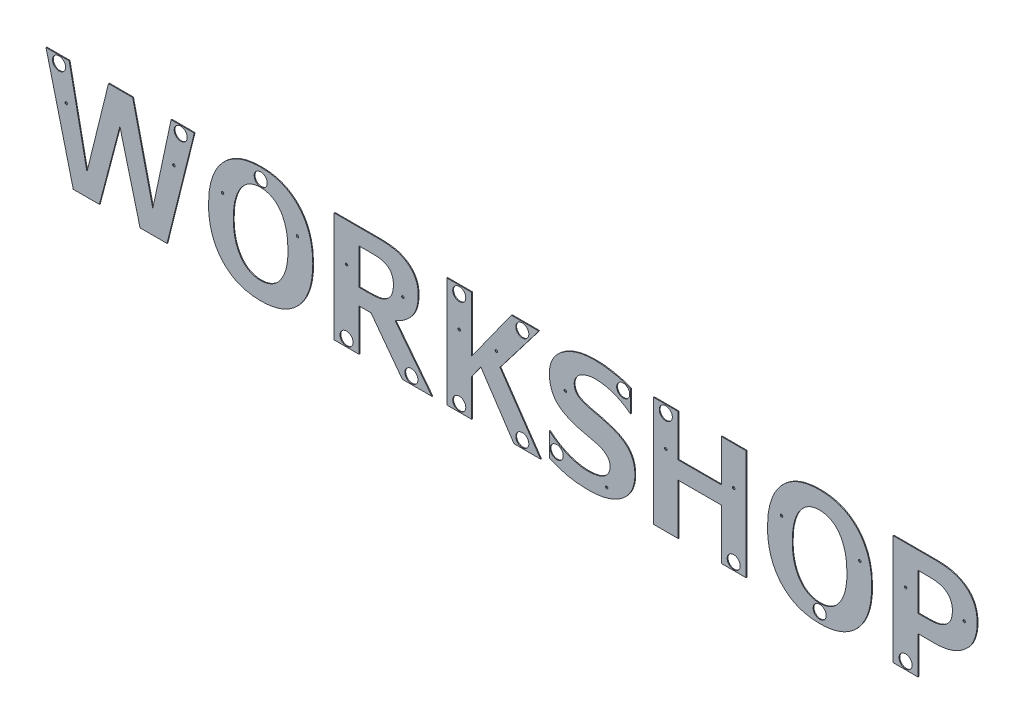
SolidWorks part; units mm, degrees
ref_plane "Front Plane" through (0, 0, 0) normal (0, 0, 1) x (1, 0, 0)
ref_plane "Top Plane" through (0, 0, 0) normal (0, 1, 0) x (1, 0, 0)
ref_plane "Right Plane" through (0, 0, 0) normal (1, 0, 0) x (0, 0, -1)
sketch "Sketch1" plane through (0, 0, 0) normal (0, 0, 1) x (1, 0, 0)
  line L26 (2759.7557, -1507.0826) -> (2731.3013, -1507.0826)
  line L27 (2731.3013, -1507.0826) -> (2708.8235, -1612.5344)
  line L28 (2708.8235, -1612.5344) -> (2684.1564, -1507.0826)
  line L29 (2684.1564, -1507.0826) -> (2654.4941, -1507.0826)
  line L30 (2654.4941, -1507.0826) -> (2628.0498, -1614.1823)
  line L31 (2628.0498, -1614.1823) -> (2606.2485, -1507.0826)
  line L32 (2606.2485, -1507.0826) -> (2577.8171, -1507.0826)
  line L33 (2577.8171, -1507.0826) -> (2611.2641, -1641.0826)
  line L34 (2611.2641, -1641.0826) -> (2643.3528, -1641.0826)
  line L35 (2643.3528, -1641.0826) -> (2668.4754, -1545.6286)
  line L36 (2668.4754, -1545.6286) -> (2693.2318, -1641.0826)
  line L37 (2693.2318, -1641.0826) -> (2726.3087, -1641.0826)
  line L38 (2726.3087, -1641.0826) -> (2759.7557, -1507.0826)
  line L39 (2759.7557, -1507.0826) -> (2731.3013, -1507.0826)
  line L40 (2731.3013, -1507.0826) -> (2708.8235, -1612.5344)
  line L41 (2708.8235, -1612.5344) -> (2684.1564, -1507.0826)
  line L42 (2684.1564, -1507.0826) -> (2654.4941, -1507.0826)
  line L43 (2654.4941, -1507.0826) -> (2628.0498, -1614.1823)
  line L44 (2628.0498, -1614.1823) -> (2606.2485, -1507.0826)
  line L45 (2606.2485, -1507.0826) -> (2577.8171, -1507.0826)
  line L46 (2577.8171, -1507.0826) -> (2611.2641, -1641.0826)
  line L47 (2611.2641, -1641.0826) -> (2643.3528, -1641.0826)
  line L48 (2643.3528, -1641.0826) -> (2668.4754, -1545.6286)
  line L49 (2668.4754, -1545.6286) -> (2693.2318, -1641.0826)
  line L50 (2693.2318, -1641.0826) -> (2726.3087, -1641.0826)
  line L51 (2726.3087, -1641.0826) -> (2759.7557, -1507.0826)
  circle A0 centre (2593.8361, -1516.0826) radius 8 construction
  circle A1 centre (2602.7021, -1553.8827) radius 1.5 construction
  circle A2 centre (2734.6463, -1553.8827) radius 1.5 construction
  circle A3 centre (2743.0722, -1516.0826) radius 8 construction
  circle A4 centre (2593.8361, -1516.0826) radius 8
  circle A5 centre (2602.7021, -1553.8827) radius 1.5
  circle A6 centre (2734.6463, -1553.8827) radius 1.5
  circle A7 centre (2743.0722, -1516.0826) radius 8
  dimension "D1" = 1
extrude "Boss-Extrude1" add sketch "Sketch1" along normal blind 1
sketch "Sketch2" plane through (0, 0, -0.5) normal (0, 0, 1) x (1, 0, 0)
  circle A0 centre (2793.9504, -1553.8827) radius 1.5 construction
  circle A1 centre (2885.8839, -1553.8827) radius 1.5 construction
  circle A2 centre (2840.7405, -1516.0826) radius 8 construction
  circle A3 centre (2793.9504, -1553.8827) radius 1.5
  circle A4 centre (2885.8839, -1553.8827) radius 1.5
  circle A5 centre (2840.7405, -1516.0826) radius 8
  spline S8 degree 3 poles (6878.5189, -1183.547) (2804.8925, -1763.4607) (2908.8116, -1656.5192) (2904.3384, -1565.1361) (2904.1495, -1562.9042) (2903.6135, -1558.4664) (2903.272, -1556.2597) (2902.4263, -1551.8728) (2901.9217, -1549.6929) (2900.7101, -1545.3662) (2899.9972, -1543.2185) (2898.7581, -1540.0309) (2898.3207, -1538.9825) (2897.4012, -1536.9114) (2896.919, -1535.8887) (2895.9015, -1533.8742) (2895.3659, -1532.8824) (2894.2343, -1530.9337) (2893.6382, -1529.9769) (2892.3912, -1528.0947) (2891.7406, -1527.1693) (2890.3877, -1525.3483) (2889.6839, -1524.4511) (2887.4952, -1521.8205) (2885.9505, -1520.1682) (2882.6781, -1517.0803) (2880.9485, -1515.6471) (2878.2208, -1513.6552) (2877.29, -1513.0169) (2875.8593, -1512.1001) (2875.3767, -1511.8013) (2874.3995, -1511.2179) (2873.9039, -1510.9328) (2871.4075, -1509.5508) (2869.3574, -1508.5899) (2865.1699, -1506.9062) (2863.0323, -1506.1838) (2859.7612, -1505.2771) (2858.6601, -1505.0042) (2856.4376, -1504.5134) (2855.3166, -1504.2958) (2851.9533, -1503.725) (2849.7007, -1503.4534) (2769.4511, -1497.8923) (2679.5563, -1618.8261) (2988.2489, 2488.8899) knots -2.419223 -2.419223 -2.419223 -2.419223 0.0625 0.0625 0.125 0.125 0.1875 0.1875 0.25 0.25 0.3125 0.3125 0.34375 0.34375 0.375 0.375 0.40625 0.40625 0.4375 0.4375 0.46875 0.46875 0.5 0.5 0.5625 0.5625 0.625 0.625 0.65625 0.65625 0.671875 0.671875 0.6875 0.6875 0.75 0.75 0.8125 0.8125 0.84375 0.84375 0.875 0.875 0.9375 0.9375 3.091034 3.091034 3.091034 3.091034 only from (2904.6404, -1574.1382) to (2840.6274, -1503.0388)
  spline S9 degree 3 poles (2350.4928, 2461.7059) (3008.2941, -1620.9883) (2909.5354, -1497.9338) (2831.639, -1503.4474) (2829.4243, -1503.7294) (2825.0269, -1504.4718) (2822.8427, -1504.9237) (2818.5192, -1506.077) (2816.381, -1506.7845) (2813.7388, -1507.8383) (2813.2113, -1508.0577) (2812.1676, -1508.5105) (2810.6158, -1509.2117) (2809.1066, -1509.9805) (2806.1465, -1511.6108) (2804.2504, -1512.8206) (2801.5128, -1514.8045) (2800.6184, -1515.4946) (2799.3056, -1516.5757) (2798.8729, -1516.9437) (2798.0173, -1517.6955) (2797.5945, -1518.0794) (2795.5209, -1520.0248) (2793.9748, -1521.6717) (2791.0782, -1525.1224) (2789.7312, -1526.9292) (2787.8635, -1529.762) (2787.2655, -1530.726) (2786.1181, -1532.693) (2785.5717, -1533.6913) (2784.5363, -1535.7067) (2784.0471, -1536.7256) (2783.1273, -1538.7863) (2782.6971, -1539.8283) (2781.8888, -1541.9327) (2781.5108, -1542.9951) (2780.7997, -1545.1375) (2780.4664, -1546.2174) (2779.8446, -1548.3949) (2779.5563, -1549.4938) (2779.0264, -1551.7039) (2778.7855, -1552.8116) (2778.1314, -1556.1423) (2777.7821, -1558.3724) (2777.2323, -1562.8492) (2777.0383, -1565.0966) (2772.4969, -1656.1152) (2877.735, -1757.0639) (-1212.3496, -1391.8139) knots -2.051378 -2.051378 -2.051378 -2.051378 0.0625 0.0625 0.125 0.125 0.1875 0.1875 0.25 0.25 0.265625 0.265625 0.28125 0.3125 0.3125 0.375 0.375 0.40625 0.40625 0.421875 0.421875 0.4375 0.4375 0.5 0.5 0.5625 0.5625 0.59375 0.59375 0.625 0.625 0.65625 0.65625 0.6875 0.6875 0.71875 0.71875 0.75 0.75 0.78125 0.78125 0.8125 0.8125 0.875 0.875 0.9375 0.9375 3.39609 3.39609 3.39609 3.39609 only from (2840.6274, -1503.0388) to (2776.7298, -1574.1381)
  spline S10 degree 3 poles (-1197.4512, -1964.9412) (2878.139, -1387.5992) (2772.4926, -1493.2331) (2777.0391, -1583.128) (2777.2354, -1585.356) (2777.7857, -1589.7864) (2778.133, -1591.9897) (2778.9951, -1596.3691) (2779.5145, -1598.5444) (2780.4394, -1601.7835) (2780.7706, -1602.8594) (2781.4829, -1605.0032) (2781.8652, -1606.0737) (2782.6808, -1608.1919) (2783.1134, -1609.237) (2784.0336, -1611.296) (2784.5209, -1612.3102) (2785.5461, -1614.3099) (2786.0839, -1615.2956) (2787.2082, -1617.2394) (2787.7948, -1618.1975) (2789.0241, -1620.082) (2789.6678, -1621.0078) (2790.6782, -1622.3712) (2791.0224, -1622.8214) (2791.7255, -1623.7137) (2792.0849, -1624.1562) (2793.906, -1626.3338) (2795.4434, -1627.9825) (2798.6953, -1631.0751) (2800.4135, -1632.5143) (2803.1305, -1634.5116) (2804.0591, -1635.1507) (2805.4874, -1636.0684) (2805.9695, -1636.3674) (2806.9457, -1636.9514) (2807.4404, -1637.2366) (2809.9259, -1638.6172) (2811.9659, -1639.5833) (2816.1398, -1641.2644) (2818.2738, -1641.9791) (2821.5401, -1642.876) (2822.6396, -1643.1462) (2824.8583, -1643.634) (2825.976, -1643.8512) (2829.3296, -1644.4289) (2831.5752, -1644.7126) (2910.0637, -1650.2753) (2998.8368, -1526.6044) (2676.208, -5636.7225) knots -2.381449 -2.381449 -2.381449 -2.381449 0.0625 0.0625 0.125 0.125 0.1875 0.1875 0.25 0.25 0.28125 0.28125 0.3125 0.3125 0.34375 0.34375 0.375 0.375 0.40625 0.40625 0.4375 0.4375 0.46875 0.46875 0.484375 0.484375 0.5 0.5 0.5625 0.5625 0.625 0.625 0.65625 0.65625 0.671875 0.671875 0.6875 0.6875 0.75 0.75 0.8125 0.8125 0.84375 0.84375 0.875 0.875 0.9375 0.9375 3.047875 3.047875 3.047875 3.047875 only from (2776.7298, -1574.1381) to (2840.6277, -1645.1263)
  spline S11 degree 3 poles (3316.4538, -5611.4168) (2669.1416, -1531.1074) (2769.3375, -1650.2079) (2849.623, -1644.7191) (2851.843, -1644.4554) (2856.2452, -1643.7158) (2858.4277, -1643.2412) (2862.7531, -1642.0705) (2864.8965, -1641.3764) (2867.5448, -1640.3346) (2868.0728, -1640.1175) (2869.1172, -1639.6687) (2870.6697, -1638.9726) (2872.1793, -1638.2078) (2875.1416, -1636.5861) (2877.0406, -1635.3829) (2879.7811, -1633.4042) (2880.6764, -1632.7153) (2882.4295, -1631.2774) (2883.2902, -1630.5256) (2885.7868, -1628.2047) (2887.3415, -1626.568) (2890.2474, -1623.1284) (2891.6014, -1621.3279) (2893.4879, -1618.5091) (2894.0917, -1617.5491) (2895.2445, -1615.5844) (2895.7883, -1614.5866) (2896.8167, -1612.5699) (2897.3021, -1611.55) (2898.2243, -1609.491) (2898.6617, -1608.4521) (2899.899, -1605.3055) (2900.6208, -1603.1668) (2901.5498, -1599.8976) (2901.8354, -1598.7962) (2902.3592, -1596.5847) (2902.597, -1595.4762) (2903.2463, -1592.1436) (2903.5949, -1589.9124) (2904.1426, -1585.4333) (2904.3355, -1583.1847) (2908.8407, -1492.0126) (2803.7102, -1390.8476) (6893.5582, -1758.9048) knots -2.115429 -2.115429 -2.115429 -2.115429 0.0625 0.0625 0.125 0.125 0.1875 0.1875 0.25 0.25 0.265625 0.265625 0.28125 0.3125 0.3125 0.375 0.375 0.40625 0.40625 0.4375 0.4375 0.5 0.5 0.5625 0.5625 0.59375 0.59375 0.625 0.625 0.65625 0.65625 0.6875 0.6875 0.75 0.75 0.78125 0.78125 0.8125 0.8125 0.875 0.875 0.9375 0.9375 3.398934 3.398934 3.398934 3.398934 only from (2840.6277, -1645.1263) to (2904.6404, -1574.1382)
  spline S12 degree 3 poles (2904.6404, -1574.1382) (2904.5994, -1571.882) (2904.5582, -1569.6258) (2904.3384, -1565.1361) (2904.1495, -1562.9042) (2903.6135, -1558.4664) (2903.272, -1556.2597) (2902.4263, -1551.8728) (2901.9217, -1549.6929) (2900.7101, -1545.3662) (2899.9972, -1543.2185) (2898.7581, -1540.0309) (2898.3207, -1538.9825) (2897.4012, -1536.9114) (2896.919, -1535.8887) (2895.9015, -1533.8742) (2895.3659, -1532.8824) (2894.2343, -1530.9337) (2893.6382, -1529.9769) (2892.3912, -1528.0947) (2891.7406, -1527.1693) (2890.3877, -1525.3483) (2889.6839, -1524.4511) (2887.4952, -1521.8205) (2885.9505, -1520.1682) (2882.6781, -1517.0803) (2880.9485, -1515.6471) (2878.2208, -1513.6552) (2877.29, -1513.0169) (2875.8593, -1512.1001) (2875.3767, -1511.8013) (2874.3995, -1511.2179) (2873.9039, -1510.9328) (2871.4075, -1509.5508) (2869.3574, -1508.5899) (2865.1699, -1506.9062) (2863.0323, -1506.1838) (2859.7612, -1505.2771) (2858.6601, -1505.0042) (2856.4376, -1504.5134) (2855.3166, -1504.2958) (2851.9533, -1503.725) (2849.7007, -1503.4534) (2845.1741, -1503.1397) (2842.9007, -1503.0893) (2840.6274, -1503.0388) knots 0 0 0 0 0.0625 0.0625 0.125 0.125 0.1875 0.1875 0.25 0.25 0.3125 0.3125 0.34375 0.34375 0.375 0.375 0.40625 0.40625 0.4375 0.4375 0.46875 0.46875 0.5 0.5 0.5625 0.5625 0.625 0.625 0.65625 0.65625 0.671875 0.671875 0.6875 0.6875 0.75 0.75 0.8125 0.8125 0.84375 0.84375 0.875 0.875 0.9375 0.9375 1 1 1 1
  spline S13 degree 3 poles (2840.6274, -1503.0388) (2838.3702, -1503.0847) (2836.113, -1503.1308) (2831.639, -1503.4474) (2829.4243, -1503.7294) (2825.0269, -1504.4718) (2822.8427, -1504.9237) (2818.5192, -1506.077) (2816.381, -1506.7845) (2813.7388, -1507.8383) (2813.2113, -1508.0577) (2812.1676, -1508.5105) (2810.6158, -1509.2117) (2809.1066, -1509.9805) (2806.1465, -1511.6108) (2804.2504, -1512.8206) (2801.5128, -1514.8045) (2800.6184, -1515.4946) (2799.3056, -1516.5757) (2798.8729, -1516.9437) (2798.0173, -1517.6955) (2797.5945, -1518.0794) (2795.5209, -1520.0248) (2793.9748, -1521.6717) (2791.0782, -1525.1224) (2789.7312, -1526.9292) (2787.8635, -1529.762) (2787.2655, -1530.726) (2786.1181, -1532.693) (2785.5717, -1533.6913) (2784.5363, -1535.7067) (2784.0471, -1536.7256) (2783.1273, -1538.7863) (2782.6971, -1539.8283) (2781.8888, -1541.9327) (2781.5108, -1542.9951) (2780.7997, -1545.1375) (2780.4664, -1546.2174) (2779.8446, -1548.3949) (2779.5563, -1549.4938) (2779.0264, -1551.7039) (2778.7855, -1552.8116) (2778.1314, -1556.1423) (2777.7821, -1558.3724) (2777.2323, -1562.8492) (2777.0383, -1565.0966) (2776.8131, -1569.6094) (2776.7714, -1571.8738) (2776.7298, -1574.1381) knots 0 0 0 0 0.0625 0.0625 0.125 0.125 0.1875 0.1875 0.25 0.25 0.265625 0.265625 0.28125 0.3125 0.3125 0.375 0.375 0.40625 0.40625 0.421875 0.421875 0.4375 0.4375 0.5 0.5 0.5625 0.5625 0.59375 0.59375 0.625 0.625 0.65625 0.65625 0.6875 0.6875 0.71875 0.71875 0.75 0.75 0.78125 0.78125 0.8125 0.8125 0.875 0.875 0.9375 0.9375 1 1 1 1
  spline S14 degree 3 poles (2776.7298, -1574.1381) (2776.771, -1576.3915) (2776.8124, -1578.6448) (2777.0391, -1583.128) (2777.2354, -1585.356) (2777.7857, -1589.7864) (2778.133, -1591.9897) (2778.9951, -1596.3691) (2779.5145, -1598.5444) (2780.4394, -1601.7835) (2780.7706, -1602.8594) (2781.4829, -1605.0032) (2781.8652, -1606.0737) (2782.6808, -1608.1919) (2783.1134, -1609.237) (2784.0336, -1611.296) (2784.5209, -1612.3102) (2785.5461, -1614.3099) (2786.0839, -1615.2956) (2787.2082, -1617.2394) (2787.7948, -1618.1975) (2789.0241, -1620.082) (2789.6678, -1621.0078) (2790.6782, -1622.3712) (2791.0224, -1622.8214) (2791.7255, -1623.7137) (2792.0849, -1624.1562) (2793.906, -1626.3338) (2795.4434, -1627.9825) (2798.6953, -1631.0751) (2800.4135, -1632.5143) (2803.1305, -1634.5116) (2804.0591, -1635.1507) (2805.4874, -1636.0684) (2805.9695, -1636.3674) (2806.9457, -1636.9514) (2807.4404, -1637.2366) (2809.9259, -1638.6172) (2811.9659, -1639.5833) (2816.1398, -1641.2644) (2818.2738, -1641.9791) (2821.5401, -1642.876) (2822.6396, -1643.1462) (2824.8583, -1643.634) (2825.976, -1643.8512) (2829.3296, -1644.4289) (2831.5752, -1644.7126) (2836.0905, -1645.0326) (2838.3591, -1645.0794) (2840.6277, -1645.1263) knots 0 0 0 0 0.0625 0.0625 0.125 0.125 0.1875 0.1875 0.25 0.25 0.28125 0.28125 0.3125 0.3125 0.34375 0.34375 0.375 0.375 0.40625 0.40625 0.4375 0.4375 0.46875 0.46875 0.484375 0.484375 0.5 0.5 0.5625 0.5625 0.625 0.625 0.65625 0.65625 0.671875 0.671875 0.6875 0.6875 0.75 0.75 0.8125 0.8125 0.84375 0.84375 0.875 0.875 0.9375 0.9375 1 1 1 1
  spline S15 degree 3 poles (2840.6277, -1645.1263) (2842.8857, -1645.076) (2845.1436, -1645.0253) (2849.623, -1644.7191) (2851.843, -1644.4554) (2856.2452, -1643.7158) (2858.4277, -1643.2412) (2862.7531, -1642.0705) (2864.8965, -1641.3764) (2867.5448, -1640.3346) (2868.0728, -1640.1175) (2869.1172, -1639.6687) (2870.6697, -1638.9726) (2872.1793, -1638.2078) (2875.1416, -1636.5861) (2877.0406, -1635.3829) (2879.7811, -1633.4042) (2880.6764, -1632.7153) (2882.4295, -1631.2774) (2883.2902, -1630.5256) (2885.7868, -1628.2047) (2887.3415, -1626.568) (2890.2474, -1623.1284) (2891.6014, -1621.3279) (2893.4879, -1618.5091) (2894.0917, -1617.5491) (2895.2445, -1615.5844) (2895.7883, -1614.5866) (2896.8167, -1612.5699) (2897.3021, -1611.55) (2898.2243, -1609.491) (2898.6617, -1608.4521) (2899.899, -1605.3055) (2900.6208, -1603.1668) (2901.5498, -1599.8976) (2901.8354, -1598.7962) (2902.3592, -1596.5847) (2902.597, -1595.4762) (2903.2463, -1592.1436) (2903.5949, -1589.9124) (2904.1426, -1585.4333) (2904.3355, -1583.1847) (2904.5587, -1578.6693) (2904.5996, -1576.4038) (2904.6404, -1574.1382) knots 0 0 0 0 0.0625 0.0625 0.125 0.125 0.1875 0.1875 0.25 0.25 0.265625 0.265625 0.28125 0.3125 0.3125 0.375 0.375 0.40625 0.40625 0.4375 0.4375 0.5 0.5 0.5625 0.5625 0.59375 0.59375 0.625 0.625 0.65625 0.65625 0.6875 0.6875 0.75 0.75 0.78125 0.78125 0.8125 0.8125 0.875 0.875 0.9375 0.9375 1 1 1 1
  spline S56 degree 3 poles (5680.9768, 1300.6585) (2859.496, -1679.2345) (2894.7539, -1569.8342) (2861.3803, -1532.9836) (2860.5791, -1532.1811) (2858.8692, -1530.6925) (2857.9574, -1530.0098) (2856.5161, -1529.0652) (2856.022, -1528.762) (2855.0239, -1528.1894) (2854.519, -1527.9194) (2851.9636, -1526.6546) (2849.8186, -1525.9214) (2847.0375, -1525.2812) (2846.4765, -1525.1663) (2845.3431, -1524.9681) (2844.7715, -1524.8852) (2801.9114, -1520.1714) (2750.1478, -1634.2331) (3034.9982, 2468.9949) knots -5.213496 -5.213496 -5.213496 -5.213496 0.125 0.125 0.25 0.25 0.375 0.375 0.4375 0.4375 0.5 0.5 0.75 0.75 0.8125 0.8125 0.875 0.875 5.497252 5.497252 5.497252 5.497252 only from (2864.3604, -1536.4361) to (2840.755, -1524.6197)
  spline S57 degree 3 poles (2231.5261, 2426.9106) (2944.3912, -1630.5217) (2880.274, -1520.8273) (2836.2188, -1524.8764) (2835.1059, -1525.0544) (2832.8989, -1525.5106) (2831.8052, -1525.7912) (2830.1866, -1526.3297) (2829.6506, -1526.5282) (2828.5855, -1526.9622) (2828.0603, -1527.1963) (2826.5188, -1527.9429) (2825.5349, -1528.5073) (2824.1371, -1529.4731) (2823.683, -1529.813) (2822.7912, -1530.5179) (2822.353, -1530.882) (2821.4889, -1531.6293) (2821.0631, -1532.0143) (2820.2361, -1532.8055) (2819.8349, -1533.2124) (2788.1474, -1567.376) (2834.9753, -1673.0529) (-213.4583, 1071.0914) knots -4.637586 -4.637586 -4.637586 -4.637586 0.125 0.125 0.25 0.25 0.375 0.375 0.4375 0.4375 0.5 0.5 0.625 0.625 0.6875 0.6875 0.75 0.75 0.8125 0.8125 0.875 0.875 5.911845 5.911845 5.911845 5.911845 only from (2840.755, -1524.6197) to (2817.2121, -1536.2317)
  spline S58 degree 3 poles (-717.2821, 332.4515) (2934.32, -1494.0312) (2841.4591, -1499.8247) (2815.3219, -1538.9778) (2814.8849, -1539.6817) (2814.0728, -1541.1194) (2813.6947, -1541.8518) (2812.9757, -1543.3348) (2812.6336, -1544.0847) (2811.9835, -1545.6012) (2811.6758, -1546.3679) (2811.0973, -1547.9192) (2810.8265, -1548.7038) (2810.3159, -1550.2881) (2810.0759, -1551.0884) (2809.6228, -1552.6922) (2809.1965, -1554.3015) (2808.8363, -1555.9244) (2808.5148, -1557.5552) (2808.3733, -1558.3747) (2808.12, -1560.0196) (2808.0081, -1560.8451) (2807.8047, -1562.5004) (2807.7125, -1563.3294) (2807.4681, -1565.8172) (2807.3511, -1567.4783) (2804.2247, -1645.7127) (2893.4903, -1727.5119) (-1187.7448, -1573.1131) knots -3.412484 -3.412484 -3.412484 -3.412484 0.0625 0.0625 0.125 0.125 0.1875 0.1875 0.25 0.25 0.3125 0.3125 0.375 0.375 0.4375 0.4375 0.5 0.5625 0.5625 0.625 0.625 0.6875 0.6875 0.75 0.75 0.875 0.875 6.626985 6.626985 6.626985 6.626985 only from (2817.2121, -1536.2317) to (2807.1722, -1574.1393)
  spline S59 degree 3 poles (-1186.5578, -1507.2156) (2887.5112, -1413.5313) (2804.3287, -1498.1586) (2807.3415, -1580.741) (2807.4419, -1582.389) (2807.7375, -1585.6808) (2807.9279, -1587.3206) (2808.416, -1590.5828) (2808.7175, -1592.2049) (2809.4645, -1595.4264) (2809.9047, -1597.0124) (2810.9228, -1600.1178) (2811.5035, -1601.6385) (2812.4783, -1603.8729) (2812.8196, -1604.6104) (2813.5362, -1606.0702) (2813.9127, -1606.792) (2814.7182, -1608.212) (2815.1503, -1608.9088) (2841.8539, -1649.3087) (2933.5696, -1659.7095) (-773.0308, -3370.7846) knots -6.007485 -6.007485 -6.007485 -6.007485 0.125 0.125 0.25 0.25 0.375 0.375 0.5 0.5 0.625 0.625 0.75 0.75 0.8125 0.8125 0.875 0.875 0.9375 0.9375 4.550375 4.550375 4.550375 4.550375 only from (2807.1722, -1574.1393) to (2817.0054, -1611.6395)
  spline S60 degree 3 poles (28.9063, -4476.9906) (2825.5889, -1467.0676) (2787.5092, -1579.1019) (2819.9852, -1615.1239) (2820.7922, -1615.9266) (2822.5036, -1617.4249) (2823.4082, -1618.1202) (2825.3225, -1619.395) (2826.3407, -1619.9763) (2829.4471, -1621.4961) (2831.6101, -1622.2375) (2834.4092, -1622.8827) (2834.9738, -1622.9978) (2836.1138, -1623.1959) (2836.6902, -1623.2787) (2879.9385, -1627.9975) (2931.3322, -1514.6071) (2671.1487, -5618.183) knots -5.055019 -5.055019 -5.055019 -5.055019 0.125 0.125 0.25 0.25 0.375 0.375 0.5 0.5 0.75 0.75 0.8125 0.8125 0.875 0.875 5.500213 5.500213 5.500213 5.500213 only from (2817.0054, -1611.6395) to (2840.7393, -1623.546)
  spline S61 degree 3 poles (3529.6311, -5561.8965) (2735.1907, -1516.0985) (2801.7481, -1627.9238) (2845.3415, -1623.2229) (2846.4674, -1623.0229) (2848.6899, -1622.4819) (2849.7868, -1622.142) (2851.417, -1621.5593) (2851.9576, -1621.3517) (2853.0317, -1620.9014) (2853.5599, -1620.6605) (2855.1102, -1619.8869) (2856.1017, -1619.3054) (2858.0114, -1618.0278) (2858.9286, -1617.3301) (2860.2396, -1616.182) (2860.6653, -1615.7829) (2861.4867, -1614.9624) (2861.8836, -1614.54) (2892.9263, -1579.4794) (2843.2896, -1473.2439) (5936.6428, -4169.9829) knots -4.522553 -4.522553 -4.522553 -4.522553 0.125 0.125 0.25 0.25 0.375 0.375 0.4375 0.4375 0.5 0.5 0.625 0.625 0.75 0.75 0.8125 0.8125 0.875 0.875 5.86305 5.86305 5.86305 5.86305 only from (2840.7393, -1623.546) to (2864.4721, -1611.4132)
  spline S62 degree 3 poles (6271.8056, -3701.9745) (2753.2257, -1664.3091) (2837.8788, -1652.7737) (2866.2794, -1608.6662) (2866.7085, -1607.9667) (2867.924, -1605.8277) (2868.6492, -1604.3539) (2869.9678, -1601.3321) (2870.5533, -1599.8003) (2871.5805, -1596.7032) (2872.0192, -1595.1358) (2872.7478, -1591.964) (2873.0348, -1590.3587) (2873.381, -1587.9298) (2873.4829, -1587.1168) (2873.6681, -1585.4861) (2873.7514, -1584.6684) (2873.896, -1583.0335) (2873.9574, -1582.2155) (2874.0561, -1580.5783) (2874.0924, -1579.7591) (2876.6226, -1500.5966) (2790.1849, -1418.0894) (6868.6688, -1530.5835) knots -3.866056 -3.866056 -3.866056 -3.866056 0.0625 0.0625 0.125 0.125 0.25 0.25 0.375 0.375 0.5 0.5 0.625 0.625 0.6875 0.6875 0.75 0.75 0.8125 0.8125 0.875 0.875 6.8488 6.8488 6.8488 6.8488 only from (2864.4721, -1611.4132) to (2874.1979, -1574.0179)
  spline S63 degree 3 poles (6868.1721, -1630.7799) (2792.9355, -1733.277) (2877.1295, -1649.2135) (2874.0209, -1567.4124) (2873.9174, -1565.7637) (2873.4555, -1560.8243) (2872.9607, -1557.5603) (2872.0097, -1553.5361) (2871.803, -1552.7358) (2871.3567, -1551.1522) (2871.1166, -1550.3678) (2870.6062, -1548.8125) (2870.3358, -1548.0416) (2869.7675, -1546.5119) (2869.4694, -1545.7532) (2868.8407, -1544.2502) (2868.5103, -1543.5058) (2867.811, -1542.0341) (2867.4413, -1541.3071) (2866.6453, -1539.8781) (2866.216, -1539.1775) (2840.2633, -1499.6798) (2747.4186, -1490.6654) (6463.8646, 203.556) knots -5.944961 -5.944961 -5.944961 -5.944961 0.125 0.125 0.25 0.25 0.5 0.5 0.5625 0.5625 0.625 0.625 0.6875 0.6875 0.75 0.75 0.8125 0.8125 0.875 0.875 0.9375 0.9375 4.45274 4.45274 4.45274 4.45274 only from (2874.1979, -1574.0179) to (2864.3604, -1536.4361)
  spline S64 degree 3 poles (2864.3604, -1536.4361) (2863.6337, -1535.5531) (2862.9074, -1534.6698) (2861.3803, -1532.9836) (2860.5791, -1532.1811) (2858.8692, -1530.6925) (2857.9574, -1530.0098) (2856.5161, -1529.0652) (2856.022, -1528.762) (2855.0239, -1528.1894) (2854.519, -1527.9194) (2851.9636, -1526.6546) (2849.8186, -1525.9214) (2847.0375, -1525.2812) (2846.4765, -1525.1663) (2845.3431, -1524.9681) (2844.7715, -1524.8852) (2843.0561, -1524.6965) (2841.9056, -1524.6576) (2840.755, -1524.6197) knots 0 0 0 0 0.125 0.125 0.25 0.25 0.375 0.375 0.4375 0.4375 0.5 0.5 0.75 0.75 0.8125 0.8125 0.875 0.875 1 1 1 1
  spline S65 degree 3 poles (2840.755, -1524.6197) (2839.6135, -1524.6441) (2838.4722, -1524.6693) (2836.2188, -1524.8764) (2835.1059, -1525.0544) (2832.8989, -1525.5106) (2831.8052, -1525.7912) (2830.1866, -1526.3297) (2829.6506, -1526.5282) (2828.5855, -1526.9622) (2828.0603, -1527.1963) (2826.5188, -1527.9429) (2825.5349, -1528.5073) (2824.1371, -1529.4731) (2823.683, -1529.813) (2822.7912, -1530.5179) (2822.353, -1530.882) (2821.4889, -1531.6293) (2821.0631, -1532.0143) (2820.2361, -1532.8055) (2819.8349, -1533.2124) (2818.6698, -1534.4686) (2817.9411, -1535.3503) (2817.2121, -1536.2317) knots 0 0 0 0 0.125 0.125 0.25 0.25 0.375 0.375 0.4375 0.4375 0.5 0.5 0.625 0.625 0.6875 0.6875 0.75 0.75 0.8125 0.8125 0.875 0.875 1 1 1 1
  spline S66 degree 3 poles (2817.2121, -1536.2317) (2816.729, -1536.9131) (2816.2455, -1537.5943) (2815.3219, -1538.9778) (2814.8849, -1539.6817) (2814.0728, -1541.1194) (2813.6947, -1541.8518) (2812.9757, -1543.3348) (2812.6336, -1544.0847) (2811.9835, -1545.6012) (2811.6758, -1546.3679) (2811.0973, -1547.9192) (2810.8265, -1548.7038) (2810.3159, -1550.2881) (2810.0759, -1551.0884) (2809.6228, -1552.6922) (2809.1965, -1554.3015) (2808.8363, -1555.9244) (2808.5148, -1557.5552) (2808.3733, -1558.3747) (2808.12, -1560.0196) (2808.0081, -1560.8451) (2807.8047, -1562.5004) (2807.7125, -1563.3294) (2807.4681, -1565.8172) (2807.3511, -1567.4783) (2807.2181, -1570.8063) (2807.1953, -1572.4728) (2807.1722, -1574.1393) knots 0 0 0 0 0.0625 0.0625 0.125 0.125 0.1875 0.1875 0.25 0.25 0.3125 0.3125 0.375 0.375 0.4375 0.4375 0.5 0.5625 0.5625 0.625 0.625 0.6875 0.6875 0.75 0.75 0.875 0.875 1 1 1 1
  spline S67 degree 3 poles (2807.1722, -1574.1393) (2807.1968, -1575.7905) (2807.2212, -1577.4417) (2807.3415, -1580.741) (2807.4419, -1582.389) (2807.7375, -1585.6808) (2807.9279, -1587.3206) (2808.416, -1590.5828) (2808.7175, -1592.2049) (2809.4645, -1595.4264) (2809.9047, -1597.0124) (2810.9228, -1600.1178) (2811.5035, -1601.6385) (2812.4783, -1603.8729) (2812.8196, -1604.6104) (2813.5362, -1606.0702) (2813.9127, -1606.792) (2814.7182, -1608.212) (2815.1503, -1608.9088) (2816.0585, -1610.2828) (2816.5322, -1610.9611) (2817.0054, -1611.6395) knots 0 0 0 0 0.125 0.125 0.25 0.25 0.375 0.375 0.5 0.5 0.625 0.625 0.75 0.75 0.8125 0.8125 0.875 0.875 0.9375 0.9375 1 1 1 1
  spline S68 degree 3 poles (2817.0054, -1611.6395) (2817.7302, -1612.5328) (2818.4548, -1613.4264) (2819.9852, -1615.1239) (2820.7922, -1615.9266) (2822.5036, -1617.4249) (2823.4082, -1618.1202) (2825.3225, -1619.395) (2826.3407, -1619.9763) (2829.4471, -1621.4961) (2831.6101, -1622.2375) (2834.4092, -1622.8827) (2834.9738, -1622.9978) (2836.1138, -1623.1959) (2836.6902, -1623.2787) (2838.4201, -1623.4674) (2839.5797, -1623.507) (2840.7393, -1623.546) knots 0 0 0 0 0.125 0.125 0.25 0.25 0.375 0.375 0.5 0.5 0.75 0.75 0.8125 0.8125 0.875 0.875 1 1 1 1
  spline S69 degree 3 poles (2840.7393, -1623.546) (2841.8988, -1623.5081) (2843.058, -1623.4692) (2845.3415, -1623.2229) (2846.4674, -1623.0229) (2848.6899, -1622.4819) (2849.7868, -1622.142) (2851.417, -1621.5593) (2851.9576, -1621.3517) (2853.0317, -1620.9014) (2853.5599, -1620.6605) (2855.1102, -1619.8869) (2856.1017, -1619.3054) (2858.0114, -1618.0278) (2858.9286, -1617.3301) (2860.2396, -1616.182) (2860.6653, -1615.7829) (2861.4867, -1614.9624) (2861.8836, -1614.54) (2863.036, -1613.2383) (2863.7539, -1612.3256) (2864.4721, -1611.4132) knots 0 0 0 0 0.125 0.125 0.25 0.25 0.375 0.375 0.4375 0.4375 0.5 0.5 0.625 0.625 0.75 0.75 0.8125 0.8125 0.875 0.875 1 1 1 1
  spline S70 degree 3 poles (2864.4721, -1611.4132) (2864.9308, -1610.7303) (2865.3899, -1610.0477) (2866.2794, -1608.6662) (2866.7085, -1607.9667) (2867.924, -1605.8277) (2868.6492, -1604.3539) (2869.9678, -1601.3321) (2870.5533, -1599.8003) (2871.5805, -1596.7032) (2872.0192, -1595.1358) (2872.7478, -1591.964) (2873.0348, -1590.3587) (2873.381, -1587.9298) (2873.4829, -1587.1168) (2873.6681, -1585.4861) (2873.7514, -1584.6684) (2873.896, -1583.0335) (2873.9574, -1582.2155) (2874.0561, -1580.5783) (2874.0924, -1579.7591) (2874.171, -1577.3002) (2874.1845, -1575.6591) (2874.1979, -1574.0179) knots 0 0 0 0 0.0625 0.0625 0.125 0.125 0.25 0.25 0.375 0.375 0.5 0.5 0.625 0.625 0.6875 0.6875 0.75 0.75 0.8125 0.8125 0.875 0.875 1 1 1 1
  spline S71 degree 3 poles (2874.1979, -1574.0179) (2874.1721, -1572.3657) (2874.1464, -1570.7135) (2874.0209, -1567.4124) (2873.9174, -1565.7637) (2873.4555, -1560.8243) (2872.9607, -1557.5603) (2872.0097, -1553.5361) (2871.803, -1552.7358) (2871.3567, -1551.1522) (2871.1166, -1550.3678) (2870.6062, -1548.8125) (2870.3358, -1548.0416) (2869.7675, -1546.5119) (2869.4694, -1545.7532) (2868.8407, -1544.2502) (2868.5103, -1543.5058) (2867.811, -1542.0341) (2867.4413, -1541.3071) (2866.6453, -1539.8781) (2866.216, -1539.1775) (2865.3092, -1537.7975) (2864.8346, -1537.1169) (2864.3604, -1536.4361) knots 0 0 0 0 0.125 0.125 0.25 0.25 0.5 0.5 0.5625 0.5625 0.625 0.625 0.6875 0.6875 0.75 0.75 0.8125 0.8125 0.875 0.875 0.9375 0.9375 1 1 1 1
  dimension "D1" = 1
  dimension "D2" = 1
extrude "Boss-Extrude2" add sketch "Sketch2" along normal blind 1 separate body
sketch "Sketch3" plane through (0, 0, -0.5) normal (0, 0, 1) x (1, 0, 0)
  line L16 (3050.8781, -1641.5826) -> (3005.7401, -1583.7672)
  line L17 (2984.2848, -1506.5826) -> (2930.9066, -1506.5826)
  line L18 (2930.9066, -1506.5826) -> (2930.9066, -1641.5826)
  line L19 (2930.9066, -1641.5826) -> (2961.3497, -1641.5826)
  line L20 (2961.3497, -1641.5826) -> (2961.3497, -1590.1902)
  line L21 (2961.3497, -1590.1902) -> (2976.0665, -1590.1902)
  line L22 (2976.0665, -1590.1902) -> (3014.5277, -1641.5826)
  line L23 (3014.5277, -1641.5826) -> (3050.8781, -1641.5826)
  line L24 (3050.8781, -1641.5826) -> (3005.7401, -1583.7672)
  line L25 (2984.2848, -1506.5826) -> (2930.9066, -1506.5826)
  line L26 (2930.9066, -1506.5826) -> (2930.9066, -1641.5826)
  line L27 (2930.9066, -1641.5826) -> (2961.3497, -1641.5826)
  line L28 (2961.3497, -1641.5826) -> (2961.3497, -1590.1902)
  line L29 (2961.3497, -1590.1902) -> (2976.0665, -1590.1902)
  line L30 (2976.0665, -1590.1902) -> (3014.5277, -1641.5826)
  line L31 (3014.5277, -1641.5826) -> (3050.8781, -1641.5826)
  line L33 (2961.3497, -1570.38) -> (2973.7444, -1570.38)
  line L34 (2961.3497, -1526.3927) -> (2961.3497, -1570.38)
  line L35 (2975.4105, -1526.3928) -> (2961.3497, -1526.3927)
  line L36 (2961.3497, -1570.38) -> (2973.7444, -1570.38)
  line L37 (2961.3497, -1526.3927) -> (2961.3497, -1570.38)
  line L38 (2975.4105, -1526.3928) -> (2961.3497, -1526.3927)
  circle A0 centre (3015.2416, -1553.8827) radius 1.5 construction
  circle A1 centre (2946.1282, -1553.8827) radius 1.5 construction
  circle A2 centre (2946.0997, -1632.5826) radius 8 construction
  circle A3 centre (3025.6702, -1632.5826) radius 8 construction
  circle A4 centre (3015.2416, -1553.8827) radius 1.5
  circle A5 centre (2946.1282, -1553.8827) radius 1.5
  circle A6 centre (2946.0997, -1632.5826) radius 8
  circle A7 centre (3025.6702, -1632.5826) radius 8
  spline S6 degree 3 poles (5005.6626, -5033.5547) (2782.2438, -1673.9459) (2902.0446, -1637.424) (3009.6717, -1581.7359) (3010.6534, -1581.2264) (3012.589, -1580.1679) (3013.5418, -1579.6173) (3015.3958, -1578.4432) (3016.2973, -1577.8198) (3018.0571, -1576.5121) (3018.9163, -1575.8288) (3020.5954, -1574.4066) (3021.4144, -1573.6663) (3023.0061, -1572.1201) (3023.7799, -1571.3127) (3025.2693, -1569.6281) (3025.976, -1568.7619) (3027.3122, -1566.9812) (3027.9435, -1566.0678) (3029.1082, -1564.1798) (3029.6393, -1563.2036) (3030.3577, -1561.6904) (3030.5839, -1561.1776) (3031.0137, -1560.1381) (3031.2179, -1559.6106) (3031.7959, -1558.0243) (3032.1365, -1556.9569) (3032.7184, -1554.8002) (3032.9586, -1553.7107) (3033.3483, -1551.5115) (3033.501, -1550.4026) (3033.7625, -1548.1751) (3033.867, -1547.0535) (3036.5317, -1493.7337) (2948.1457, -1437.8626) (7031.4021, -1550.4093) knots -6.721385 -6.721385 -6.721385 -6.721385 0.0625 0.0625 0.125 0.125 0.1875 0.1875 0.25 0.25 0.3125 0.3125 0.375 0.375 0.4375 0.4375 0.5 0.5 0.5625 0.5625 0.625 0.625 0.65625 0.65625 0.6875 0.6875 0.75 0.75 0.8125 0.8125 0.875 0.875 0.9375 0.9375 3.844249 3.844249 3.844249 3.844249 only from (3005.7401, -1583.7672) to (3034.0075, -1542.5608)
  spline S7 degree 3 poles (7012.2559, -1153.6116) (2933.4802, -1665.0308) (3038.0645, -1594.086) (3033.7709, -1537.582) (3033.6977, -1536.8762) (3033.5072, -1535.4708) (3033.3907, -1534.7711) (3033.118, -1533.3771) (3032.9624, -1532.6828) (3032.6097, -1531.3) (3032.411, -1530.609) (3031.9575, -1529.2474) (3031.7033, -1528.5816) (3031.1358, -1527.2823) (3030.8242, -1526.6479) (3029.8213, -1524.782) (3029.0667, -1523.5851) (3027.8124, -1521.8566) (3027.3715, -1521.2902) (3026.4593, -1520.1921) (3025.9877, -1519.6597) (3024.5315, -1518.1066) (3023.5095, -1517.126) (2986.1826, -1486.76) (2858.2528, -1554.2936) (5734.6064, 1420.6945) knots -4.797179 -4.797179 -4.797179 -4.797179 0.125 0.125 0.1875 0.1875 0.25 0.25 0.3125 0.3125 0.375 0.375 0.4375 0.4375 0.5 0.5 0.625 0.625 0.6875 0.6875 0.75 0.75 0.875 0.875 4.98699 4.98699 4.98699 4.98699 only from (3034.0075, -1542.5608) to (3018.9373, -1513.7233)
  spline S8 degree 3 poles (4896.1277, 2015.7961) (3046.0819, -1675.2253) (3059.6756, -1533.4822) (3013.6821, -1510.8711) (3012.2968, -1510.3051) (3010.1758, -1509.5446) (3009.4641, -1509.3094) (3008.0307, -1508.8853) (3007.3085, -1508.697) (3005.1276, -1508.196) (3003.6556, -1507.9412) (3000.6934, -1507.5113) (2999.2055, -1507.3367) (2996.2303, -1507.0355) (2994.7411, -1506.9136) (2991.7588, -1506.7313) (2990.2658, -1506.6709) (2904.3933, -1504.73) (2815.5459, -1577.4118) (2974.6094, 2487.1663) knots -4.039923 -4.039923 -4.039923 -4.039923 0.125 0.125 0.25 0.25 0.3125 0.3125 0.375 0.375 0.5 0.5 0.625 0.625 0.75 0.75 0.875 0.875 7.932098 7.932098 7.932098 7.932098 only from (3018.9373, -1513.7233) to (2984.2848, -1506.5826)
  spline S9 degree 3 poles (3005.7401, -1583.7672) (3006.723, -1583.2594) (3007.7067, -1582.7526) (3009.6717, -1581.7359) (3010.6534, -1581.2264) (3012.589, -1580.1679) (3013.5418, -1579.6173) (3015.3958, -1578.4432) (3016.2973, -1577.8198) (3018.0571, -1576.5121) (3018.9163, -1575.8288) (3020.5954, -1574.4066) (3021.4144, -1573.6663) (3023.0061, -1572.1201) (3023.7799, -1571.3127) (3025.2693, -1569.6281) (3025.976, -1568.7619) (3027.3122, -1566.9812) (3027.9435, -1566.0678) (3029.1082, -1564.1798) (3029.6393, -1563.2036) (3030.3577, -1561.6904) (3030.5839, -1561.1776) (3031.0137, -1560.1381) (3031.2179, -1559.6106) (3031.7959, -1558.0243) (3032.1365, -1556.9569) (3032.7184, -1554.8002) (3032.9586, -1553.7107) (3033.3483, -1551.5115) (3033.501, -1550.4026) (3033.7625, -1548.1751) (3033.867, -1547.0535) (3033.9791, -1544.8089) (3033.9932, -1543.6848) (3034.0075, -1542.5608) knots 0 0 0 0 0.0625 0.0625 0.125 0.125 0.1875 0.1875 0.25 0.25 0.3125 0.3125 0.375 0.375 0.4375 0.4375 0.5 0.5 0.5625 0.5625 0.625 0.625 0.65625 0.65625 0.6875 0.6875 0.75 0.75 0.8125 0.8125 0.875 0.875 0.9375 0.9375 1 1 1 1
  spline S10 degree 3 poles (3034.0075, -1542.5608) (3033.9699, -1541.1341) (3033.9324, -1539.7074) (3033.7709, -1537.582) (3033.6977, -1536.8762) (3033.5072, -1535.4708) (3033.3907, -1534.7711) (3033.118, -1533.3771) (3032.9624, -1532.6828) (3032.6097, -1531.3) (3032.411, -1530.609) (3031.9575, -1529.2474) (3031.7033, -1528.5816) (3031.1358, -1527.2823) (3030.8242, -1526.6479) (3029.8213, -1524.782) (3029.0667, -1523.5851) (3027.8124, -1521.8566) (3027.3715, -1521.2902) (3026.4593, -1520.1921) (3025.9877, -1519.6597) (3024.5315, -1518.1066) (3023.5095, -1517.126) (3021.307, -1515.3343) (3020.1211, -1514.5281) (3018.9373, -1513.7233) knots 0 0 0 0 0.125 0.125 0.1875 0.1875 0.25 0.25 0.3125 0.3125 0.375 0.375 0.4375 0.4375 0.5 0.5 0.625 0.625 0.6875 0.6875 0.75 0.75 0.875 0.875 1 1 1 1
  spline S11 degree 3 poles (3018.9373, -1513.7233) (3017.6501, -1512.9555) (3016.3624, -1512.1888) (3013.6821, -1510.8711) (3012.2968, -1510.3051) (3010.1758, -1509.5446) (3009.4641, -1509.3094) (3008.0307, -1508.8853) (3007.3085, -1508.697) (3005.1276, -1508.196) (3003.6556, -1507.9412) (3000.6934, -1507.5113) (2999.2055, -1507.3367) (2996.2303, -1507.0355) (2994.7411, -1506.9136) (2991.7588, -1506.7313) (2990.2658, -1506.6709) (2987.2767, -1506.6033) (2985.7808, -1506.593) (2984.2848, -1506.5826) knots 0 0 0 0 0.125 0.125 0.25 0.25 0.3125 0.3125 0.375 0.375 0.5 0.5 0.625 0.625 0.75 0.75 0.875 0.875 1 1 1 1
  spline S35 degree 3 poles (4369.3573, 2224.9478) (3044.3897, -1627.3522) (3029.9317, -1541.4495) (2990.6251, -1527.7946) (2989.8929, -1527.5705) (2988.3996, -1527.2089) (2987.6455, -1527.0696) (2986.1301, -1526.8513) (2985.3678, -1526.7739) (2984.221, -1526.6822) (2983.8383, -1526.6556) (2983.0731, -1526.6031) (2982.6905, -1526.5767) (2981.5425, -1526.5038) (2980.7767, -1526.4673) (2979.2441, -1526.4288) (2978.4773, -1526.4227) (2806.8506, -1524.6932) (2635.2628, -1544.6155) (2598.0032, 2429.9791) knots -6.543894 -6.543894 -6.543894 -6.543894 0.125 0.125 0.25 0.25 0.375 0.375 0.5 0.5 0.5625 0.5625 0.625 0.625 0.75 0.75 0.875 0.875 28.731191 28.731191 28.731191 28.731191 only from (2993.5012, -1528.8496) to (2975.4105, -1526.3928)
  spline S36 degree 3 poles (6968.943, -1031.7876) (2904.1947, -1634.1158) (3006.6513, -1580.69) (3003.3807, -1542.9943) (3003.2389, -1542.1093) (3002.8807, -1540.3512) (3002.6691, -1539.4772) (3002.2387, -1538.1841) (3002.0757, -1537.7567) (3001.7207, -1536.9227) (3001.5281, -1536.5139) (3000.9126, -1535.3078) (3000.4529, -1534.5306) (2999.6294, -1533.4373) (2999.3341, -1533.0868) (2998.7179, -1532.4228) (2998.3954, -1532.1072) (2997.3923, -1531.2014) (2996.6751, -1530.6529) (2995.5177, -1529.9235) (2995.1197, -1529.697) (2965.6832, -1513.8522) (2910.2558, -1546.9956) (4810.322, 2033.4213) knots -5.014527 -5.014527 -5.014527 -5.014527 0.125 0.125 0.25 0.25 0.375 0.375 0.4375 0.4375 0.5 0.5 0.625 0.625 0.6875 0.6875 0.75 0.75 0.875 0.875 0.9375 0.9375 5.450162 5.450162 5.450162 5.450162 only from (3003.5653, -1546.5943) to (2993.5012, -1528.8496)
  spline S37 degree 3 poles (6017.8217, -4184.1198) (2862.8053, -1538.2043) (2974.7385, -1587.2762) (2998.579, -1562.5793) (2999.1193, -1561.9261) (3000.1107, -1560.5461) (3000.562, -1559.8196) (3001.3802, -1558.2967) (3001.7366, -1557.5151) (3002.3376, -1555.9197) (3002.5821, -1555.1042) (3002.9706, -1553.4414) (3003.1181, -1552.593) (3003.3501, -1550.8865) (3003.4309, -1550.0307) (3006.0022, -1504.5537) (2927.6331, -1454.2132) (6998.8673, -1697.3823) knots -4.796398 -4.796398 -4.796398 -4.796398 0.125 0.125 0.25 0.25 0.375 0.375 0.5 0.5 0.625 0.625 0.75 0.75 0.875 0.875 7.375031 7.375031 7.375031 7.375031 only from (2996.1002, -1564.93) to (3003.5653, -1546.5943)
  spline S38 degree 3 poles (2888.3119, -5565.3618) (2838.2612, -1452.0399) (2910.7843, -1574.5516) (2980.618, -1570.1558) (2981.5966, -1570.0661) (2983.0607, -1569.9033) (2983.5483, -1569.8453) (2984.5228, -1569.7227) (2985.0095, -1569.6569) (2985.9806, -1569.5042) (2986.4648, -1569.4172) (2987.4218, -1569.215) (2987.8955, -1569.1004) (2989.3006, -1568.7105) (2990.2151, -1568.3873) (2991.5562, -1567.8149) (2991.9985, -1567.6105) (2992.8713, -1567.1684) (2993.3037, -1566.9291) (2994.1402, -1566.4107) (2994.5435, -1566.1305) (3020.1502, -1547.0316) (3007.7175, -1475.2121) (5386.3946, -4770.6632) knots -8.52247 -8.52247 -8.52247 -8.52247 0.25 0.25 0.375 0.375 0.4375 0.4375 0.5 0.5 0.5625 0.5625 0.625 0.625 0.75 0.75 0.8125 0.8125 0.875 0.875 0.9375 0.9375 4.939542 4.939542 4.939542 4.939542 only from (2973.7444, -1570.38) to (2996.1002, -1564.93)
  spline S39 degree 3 poles (2993.5012, -1528.8496) (2992.7862, -1528.5738) (2992.0715, -1528.2971) (2990.6251, -1527.7946) (2989.8929, -1527.5705) (2988.3996, -1527.2089) (2987.6455, -1527.0696) (2986.1301, -1526.8513) (2985.3678, -1526.7739) (2984.221, -1526.6822) (2983.8383, -1526.6556) (2983.0731, -1526.6031) (2982.6905, -1526.5767) (2981.5425, -1526.5038) (2980.7767, -1526.4673) (2979.2441, -1526.4288) (2978.4773, -1526.4227) (2976.9439, -1526.4073) (2976.1772, -1526.4) (2975.4105, -1526.3928) knots 0 0 0 0 0.125 0.125 0.25 0.25 0.375 0.375 0.5 0.5 0.5625 0.5625 0.625 0.625 0.75 0.75 0.875 0.875 1 1 1 1
  spline S40 degree 3 poles (3003.5653, -1546.5943) (3003.5512, -1545.6892) (3003.536, -1544.7844) (3003.3807, -1542.9943) (3003.2389, -1542.1093) (3002.8807, -1540.3512) (3002.6691, -1539.4772) (3002.2387, -1538.1841) (3002.0757, -1537.7567) (3001.7207, -1536.9227) (3001.5281, -1536.5139) (3000.9126, -1535.3078) (3000.4529, -1534.5306) (2999.6294, -1533.4373) (2999.3341, -1533.0868) (2998.7179, -1532.4228) (2998.3954, -1532.1072) (2997.3923, -1531.2014) (2996.6751, -1530.6529) (2995.5177, -1529.9235) (2995.1197, -1529.697) (2994.3154, -1529.2641) (2993.9082, -1529.057) (2993.5012, -1528.8496) knots 0 0 0 0 0.125 0.125 0.25 0.25 0.375 0.375 0.4375 0.4375 0.5 0.5 0.625 0.625 0.6875 0.6875 0.75 0.75 0.875 0.875 0.9375 0.9375 1 1 1 1
  spline S41 degree 3 poles (2996.1002, -1564.93) (2996.7502, -1564.3673) (2997.3979, -1563.8028) (2998.579, -1562.5793) (2999.1193, -1561.9261) (3000.1107, -1560.5461) (3000.562, -1559.8196) (3001.3802, -1558.2967) (3001.7366, -1557.5151) (3002.3376, -1555.9197) (3002.5821, -1555.1042) (3002.9706, -1553.4414) (3003.1181, -1552.593) (3003.3501, -1550.8865) (3003.4309, -1550.0307) (3003.5279, -1548.3146) (3003.5465, -1547.4544) (3003.5653, -1546.5943) knots 0 0 0 0 0.125 0.125 0.25 0.25 0.375 0.375 0.5 0.5 0.625 0.625 0.75 0.75 0.875 0.875 1 1 1 1
  spline S42 degree 3 poles (2973.7444, -1570.38) (2975.7096, -1570.3616) (2977.6747, -1570.3411) (2980.618, -1570.1558) (2981.5966, -1570.0661) (2983.0607, -1569.9033) (2983.5483, -1569.8453) (2984.5228, -1569.7227) (2985.0095, -1569.6569) (2985.9806, -1569.5042) (2986.4648, -1569.4172) (2987.4218, -1569.215) (2987.8955, -1569.1004) (2989.3006, -1568.7105) (2990.2151, -1568.3873) (2991.5562, -1567.8149) (2991.9985, -1567.6105) (2992.8713, -1567.1684) (2993.3037, -1566.9291) (2994.1402, -1566.4107) (2994.5435, -1566.1305) (2995.331, -1565.5432) (2995.7156, -1565.2365) (2996.1002, -1564.93) knots 0 0 0 0 0.25 0.25 0.375 0.375 0.4375 0.4375 0.5 0.5 0.5625 0.5625 0.625 0.625 0.75 0.75 0.8125 0.8125 0.875 0.875 0.9375 0.9375 1 1 1 1
  dimension "D1" = 1
  dimension "D2" = 1
extrude "Boss-Extrude3" add sketch "Sketch3" along normal blind 1 separate body
sketch "Sketch4" plane through (0, 0, -0.5) normal (0, 0, 1) x (1, 0, 0)
  line L24 (3184.1664, -1641.5826) -> (3134.3509, -1568.963)
  line L25 (3134.3509, -1568.963) -> (3182.0801, -1506.5826)
  line L26 (3182.0801, -1506.5826) -> (3148.2748, -1506.5826)
  line L27 (3148.2748, -1506.5826) -> (3099.5775, -1574.5546)
  line L28 (3099.5775, -1574.5546) -> (3099.5775, -1506.5826)
  line L29 (3099.5775, -1506.5826) -> (3069.1345, -1506.5826)
  line L30 (3069.1345, -1506.5826) -> (3069.1345, -1641.5826)
  line L31 (3069.1345, -1641.5826) -> (3099.5775, -1641.5826)
  line L32 (3099.5775, -1641.5826) -> (3099.5775, -1596.0386)
  line L33 (3099.5775, -1596.0386) -> (3110.8518, -1580.348)
  line L34 (3110.8518, -1580.348) -> (3151.5701, -1641.5826)
  line L35 (3151.5701, -1641.5826) -> (3184.1664, -1641.5826)
  line L36 (3184.1664, -1641.5826) -> (3134.3509, -1568.963)
  line L37 (3134.3509, -1568.963) -> (3182.0801, -1506.5826)
  line L38 (3182.0801, -1506.5826) -> (3148.2748, -1506.5826)
  line L39 (3148.2748, -1506.5826) -> (3099.5775, -1574.5546)
  line L40 (3099.5775, -1574.5546) -> (3099.5775, -1506.5826)
  line L41 (3099.5775, -1506.5826) -> (3069.1345, -1506.5826)
  line L42 (3069.1345, -1506.5826) -> (3069.1345, -1641.5826)
  line L43 (3069.1345, -1641.5826) -> (3099.5775, -1641.5826)
  line L44 (3099.5775, -1641.5826) -> (3099.5775, -1596.0386)
  line L45 (3099.5775, -1596.0386) -> (3110.8518, -1580.348)
  line L46 (3110.8518, -1580.348) -> (3151.5701, -1641.5826)
  line L47 (3151.5701, -1641.5826) -> (3184.1664, -1641.5826)
  circle A0 centre (3084.356, -1516.0826) radius 8 construction
  circle A1 centre (3084.356, -1553.8827) radius 1.5 construction
  circle A2 centre (3084.356, -1632.5826) radius 8 construction
  circle A3 centre (3161.7052, -1632.5826) radius 8 construction
  circle A4 centre (3129.955, -1553.8827) radius 1.5 construction
  circle A5 centre (3161.7052, -1516.0826) radius 8 construction
  circle A6 centre (3084.356, -1516.0826) radius 8
  circle A7 centre (3084.356, -1553.8827) radius 1.5
  circle A8 centre (3084.356, -1632.5826) radius 8
  circle A9 centre (3161.7052, -1632.5826) radius 8
  circle A10 centre (3129.955, -1553.8827) radius 1.5
  circle A11 centre (3161.7052, -1516.0826) radius 8
  dimension "D1" = 1
extrude "Boss-Extrude4" add sketch "Sketch4" along normal blind 1 separate body
sketch "Sketch5" plane through (0, 0, -0.5) normal (0, 0, 1) x (1, 0, 0)
  line L8 (3294.5142, -1538.5653) -> (3294.5142, -1511.4815)
  line L9 (3194.9573, -1606.0594) -> (3194.9573, -1635.1332)
  line L10 (3294.5142, -1538.5653) -> (3294.5142, -1511.4815)
  line L11 (3194.9573, -1606.0594) -> (3194.9573, -1635.1332)
  circle A0 centre (3203.9573, -1624.1931) radius 8 construction
  circle A1 centre (3265.2173, -1631.0062) radius 1.5 construction
  circle A2 centre (3214.5663, -1553.8827) radius 1.5 construction
  circle A3 centre (3285.5142, -1518.0227) radius 8 construction
  circle A4 centre (3203.9573, -1624.1931) radius 8
  circle A5 centre (3265.2173, -1631.0062) radius 1.5
  circle A6 centre (3214.5663, -1553.8827) radius 1.5
  circle A7 centre (3285.5142, -1518.0227) radius 8
  spline S32 degree 3 poles (3705.6514, -5612.9146) (3075.812, -1559.1766) (3169.7532, -1648.1497) (3248.4455, -1644.975) (3249.2879, -1644.9293) (3250.9678, -1644.8092) (3251.8053, -1644.7356) (3254.3116, -1644.4785) (3255.9745, -1644.2616) (3259.284, -1643.7344) (3260.9302, -1643.4216) (3264.2008, -1642.6717) (3265.8252, -1642.2344) (3269.0486, -1641.2142) (3270.6478, -1640.6327) (3273.821, -1639.3254) (3275.374, -1638.6078) (3278.3899, -1637.0304) (3279.8547, -1636.1697) (3282.6868, -1634.286) (3284.055, -1633.2643) (3286.0372, -1631.6151) (3286.6821, -1631.0492) (3287.9336, -1629.8889) (3288.5409, -1629.2935) (3289.7173, -1628.0715) (3290.2862, -1627.4445) (3291.3784, -1626.1532) (3291.9014, -1625.4885) (3293.4016, -1623.4379) (3294.3133, -1621.9982) (3295.5454, -1619.7272) (3295.9302, -1618.9556) (3296.6404, -1617.399) (3296.9672, -1616.6118) (3297.8646, -1614.2238) (3298.352, -1612.5966) (3298.9283, -1610.1068) (3299.0951, -1609.2689) (3299.3748, -1607.5759) (3299.4878, -1606.7193) (3305.0779, -1549.2824) (3178.7214, -1484.2746) (7295.9262, -1690.4735) knots -2.81835 -2.81835 -2.81835 -2.81835 0.0625 0.0625 0.09375 0.09375 0.125 0.125 0.1875 0.1875 0.25 0.25 0.3125 0.3125 0.375 0.375 0.4375 0.4375 0.5 0.5 0.5625 0.5625 0.59375 0.59375 0.625 0.625 0.65625 0.65625 0.6875 0.6875 0.75 0.75 0.78125 0.78125 0.8125 0.8125 0.875 0.875 0.90625 0.90625 0.9375 0.9375 3.001672 3.001672 3.001672 3.001672 only from (3242.5192, -1645.1266) to (3299.8301, -1600.7078)
  spline S33 degree 3 poles (7270.5608, -1139.3892) (3221.9566, -1713.3778) (3302.2556, -1649.1307) (3299.6975, -1596.6793) (3299.6128, -1595.6801) (3299.3759, -1593.6922) (3299.2252, -1592.7033) (3298.8521, -1590.7364) (3298.6303, -1589.7584) (3298.2299, -1588.3019) (3298.0847, -1587.8183) (3297.7706, -1586.8545) (3297.6015, -1586.3733) (3297.0657, -1584.947) (3296.6741, -1584.0156) (3295.7839, -1582.2132) (3295.2828, -1581.3436) (3294.1925, -1579.6542) (3293.6019, -1578.8352) (3292.6358, -1577.6518) (3292.3019, -1577.2652) (3291.621, -1576.5125) (3291.2729, -1576.1453) (3290.2091, -1575.0669) (3289.4705, -1574.3831) (3287.9349, -1573.0852) (3287.1399, -1572.4687) (3285.5081, -1571.2857) (3284.6719, -1570.7184) (3283.3852, -1569.9062) (3282.9503, -1569.642) (3282.0727, -1569.1331) (3281.6293, -1568.8884) (3280.7361, -1568.4129) (3280.2862, -1568.182) (3279.3827, -1567.7281) (3278.9294, -1567.5045) (3277.5634, -1566.8466) (3276.6434, -1566.4278) (3227.0099, -1546.0001) (3143.5733, -1599.7107) (4834.969, 2114.6679) knots -3.137927 -3.137927 -3.137927 -3.137927 0.0625 0.0625 0.125 0.125 0.1875 0.1875 0.25 0.25 0.28125 0.28125 0.3125 0.3125 0.375 0.375 0.4375 0.4375 0.5 0.5 0.53125 0.53125 0.5625 0.5625 0.625 0.625 0.6875 0.6875 0.75 0.75 0.78125 0.78125 0.8125 0.8125 0.84375 0.84375 0.875 0.875 0.9375 0.9375 4.18979 4.18979 4.18979 4.18979 only from (3299.8301, -1600.7078) to (3272.8745, -1564.9416)
  spline S34 degree 3 poles (4767.1627, 2138.9242) (3389.761, -1725.8095) (3346.9641, -1587.3311) (3263.965, -1562.033) (3261.6964, -1561.4473) (3095.1556, -1520.2904) (2904.1435, -1593.3486) (3672.4085, 2395.5046) knots -8.755153 -8.755153 -8.755153 -8.755153 0.25 0.25 0.5 0.5 18.553481 18.553481 18.553481 18.553481 only from (3272.8745, -1564.9416) to (3245.7328, -1557.6851)
  spline S35 degree 3 poles (2350.0236, -5452.0122) (3393.4733, -1517.6654) (3307.2871, -1574.5655) (3241.0784, -1556.4646) (3239.9234, -1556.1291) (3238.2124, -1555.5497) (3237.6471, -1555.3417) (3236.5243, -1554.9121) (3235.9648, -1554.6933) (3234.8541, -1554.238) (3234.305, -1553.9969) (3233.2288, -1553.4676) (3232.7008, -1553.1812) (3231.6669, -1552.5613) (3231.1572, -1552.2272) (3230.1876, -1551.5076) (3229.7293, -1551.1196) (3228.8739, -1550.2783) (3228.4751, -1549.8269) (3227.7349, -1548.863) (3227.401, -1548.3596) (3226.8109, -1547.3157) (3226.5544, -1546.7739) (3226.1219, -1545.6489) (3225.9449, -1545.0628) (3225.6774, -1543.8856) (3225.5876, -1543.2907) (3222.3052, -1511.0796) (3296.3646, -1468.205) (-744.0201, -2024.9635) knots -6.883341 -6.883341 -6.883341 -6.883341 0.125 0.125 0.25 0.25 0.3125 0.3125 0.375 0.375 0.4375 0.4375 0.5 0.5 0.5625 0.5625 0.625 0.625 0.6875 0.6875 0.75 0.75 0.8125 0.8125 0.875 0.875 0.9375 0.9375 4.235078 4.235078 4.235078 4.235078 only from (3245.7328, -1557.6851) to (3225.3981, -1540.8861)
  spline S36 degree 3 poles (-731.522, -960.7415) (3333.3031, -1613.9899) (3221.5375, -1566.6005) (3225.6599, -1537.8922) (3225.8471, -1537.1642) (3226.1975, -1536.0838) (3226.3248, -1535.7252) (3226.6025, -1535.0241) (3226.7535, -1534.6806) (3227.2509, -1533.6755) (3227.6449, -1533.0413) (3228.5165, -1531.821) (3228.9946, -1531.2298) (3230.0051, -1530.1144) (3230.5377, -1529.5884) (3231.6593, -1528.6016) (3232.2474, -1528.1397) (3258.136, -1510.8695) (3353.6343, -1577.0535) (521.9671, 1411.9325) knots -4.589039 -4.589039 -4.589039 -4.589039 0.125 0.125 0.25 0.25 0.3125 0.3125 0.375 0.375 0.5 0.5 0.625 0.625 0.75 0.75 0.875 0.875 5.917675 5.917675 5.917675 5.917675 only from (3225.3981, -1540.8861) to (3234.836, -1526.574)
  spline S37 degree 3 poles (1529.0339, 2089.0645) (3196.97, -1678.9138) (3192.2952, -1542.0108) (3240.2875, -1524.3193) (3241.7051, -1523.9202) (3244.5955, -1523.3198) (3246.0514, -1523.1221) (3301.6632, -1518.8769) (3366.0255, -1632.4976) (3064.7061, 2470.0977) knots -8.159616 -8.159616 -8.159616 -8.159616 0.25 0.25 0.5 0.5 0.75 0.75 10.006457 10.006457 10.006457 10.006457 only from (3234.836, -1526.574) to (3251.9163, -1522.8479)
  spline S38 degree 3 poles (3452.4914, 2468.4525) (3116.8397, -1644.1141) (3193.7032, -1517.5567) (3259.6346, -1523.2761) (3261.5462, -1523.568) (3265.354, -1524.3105) (3267.236, -1524.7517) (3270.9298, -1525.8103) (3272.7409, -1526.4348) (3276.3127, -1527.8187) (3278.076, -1528.5708) (3280.6843, -1529.7969) (3281.5473, -1530.2228) (3283.2602, -1531.1094) (3284.1112, -1531.5705) (3286.6379, -1532.9991) (3288.2885, -1534.0014) (3290.6836, -1535.6238) (3291.4667, -1536.1871) (3341.3548, -1574.0141) (3336.8454, -1690.2247) (5687.8934, 1662.1036) knots -4.034006 -4.034006 -4.034006 -4.034006 0.125 0.125 0.25 0.25 0.375 0.375 0.5 0.5 0.625 0.625 0.6875 0.6875 0.75 0.75 0.875 0.875 0.9375 0.9375 4.92734 4.92734 4.92734 4.92734 only from (3251.9163, -1522.8479) to (3294.5142, -1538.5653)
  spline S39 degree 3 poles (4787.4709, 2194.777) (3391.0039, -1642.4463) (3355.7111, -1535.0907) (3291.0039, -1510.0833) (3290.1176, -1509.7591) (3287.4416, -1508.8359) (3285.6371, -1508.2797) (3280.1829, -1506.7292) (3276.5013, -1505.8795) (3270.9334, -1504.8134) (3269.0707, -1504.498) (3265.3385, -1503.9713) (3263.468, -1503.7556) (3259.7202, -1503.4004) (3257.8426, -1503.2639) (3173.2284, -1499.5976) (3081.6379, -1593.495) (3369.6092, 2489.2273) knots -4.466796 -4.466796 -4.466796 -4.466796 0.0625 0.0625 0.125 0.125 0.25 0.25 0.5 0.5 0.625 0.625 0.75 0.75 0.875 0.875 6.36807 6.36807 6.36807 6.36807 only from (3294.5142, -1511.4815) to (3250.3029, -1503.0386)
  spline S40 degree 3 poles (2850.9429, 2472.3222) (3405.4682, -1590.9041) (3318.16, -1499.7865) (3243.84, -1503.2457) (3242.2363, -1503.3749) (3239.045, -1503.7384) (3237.457, -1503.9696) (3234.296, -1504.5287) (3232.7228, -1504.8556) (3229.5938, -1505.6224) (3228.0385, -1506.0647) (3225.7221, -1506.836) (3224.9529, -1507.1112) (3223.435, -1507.6914) (3222.6844, -1507.9972) (3220.4563, -1508.9594) (3219.0009, -1509.6573) (3216.145, -1511.1568) (3214.7483, -1511.9652) (3212.7134, -1513.2914) (3212.0444, -1513.7508) (3210.7238, -1514.7027) (3210.071, -1515.1965) (3208.1549, -1516.7147) (3206.9326, -1517.7806) (3204.6257, -1520.0466) (3203.5396, -1521.2452) (3202.0239, -1523.1537) (3201.5375, -1523.8083) (3200.6059, -1525.1576) (3200.1666, -1525.8441) (3198.9304, -1527.9379) (3198.2193, -1529.3823) (3197.0095, -1532.3622) (3196.5075, -1533.8963) (3195.9034, -1536.2613) (3195.7258, -1537.0625) (3195.4294, -1538.6676) (3195.3102, -1539.473) (3189.5766, -1592.1237) (3319.9442, -1657.6213) (-794.8907, -1296.9056) knots -2.756307 -2.756307 -2.756307 -2.756307 0.0625 0.0625 0.125 0.125 0.1875 0.1875 0.25 0.25 0.3125 0.3125 0.34375 0.34375 0.375 0.375 0.4375 0.4375 0.5 0.5 0.53125 0.53125 0.5625 0.5625 0.625 0.625 0.6875 0.6875 0.71875 0.71875 0.75 0.75 0.8125 0.8125 0.875 0.875 0.90625 0.90625 0.9375 0.9375 2.941149 2.941149 2.941149 2.941149 only from (3250.3029, -1503.0386) to (3194.9579, -1545.1594)
  spline S41 degree 3 poles (-769.2207, -2060.9456) (3276.4805, -1429.729) (3192.3726, -1496.3779) (3195.104, -1549.425) (3195.1982, -1550.4817) (3195.4618, -1552.5823) (3195.6315, -1553.6261) (3196.0322, -1555.7036) (3196.2597, -1556.7377) (3196.8198, -1558.7882) (3197.1562, -1559.8039) (3197.7227, -1561.3171) (3197.9214, -1561.8188) (3198.3419, -1562.8061) (3198.564, -1563.2928) (3199.0369, -1564.2492) (3199.2871, -1564.7193) (3199.806, -1565.6485) (3200.0739, -1566.1082) (3200.6273, -1567.017) (3200.9134, -1567.4659) (3201.5156, -1568.346) (3201.8332, -1568.7763) (3202.4981, -1569.6194) (3202.8457, -1570.0332) (3203.5594, -1570.8442) (3203.9243, -1571.2403) (3205.0445, -1572.3986) (3205.8269, -1573.1288) (3207.4574, -1574.5121) (3208.3043, -1575.1664) (3210.0496, -1576.4147) (3210.9498, -1577.0112) (3213.6998, -1578.7026) (3215.6009, -1579.6885) (3218.514, -1581.0389) (3219.4972, -1581.4636) (3277.0223, -1604.5878) (3365.9871, -1559.5605) (1661.1288, -5261.5683) knots -2.993011 -2.993011 -2.993011 -2.993011 0.0625 0.0625 0.125 0.125 0.1875 0.1875 0.25 0.25 0.3125 0.3125 0.34375 0.34375 0.375 0.375 0.40625 0.40625 0.4375 0.4375 0.46875 0.46875 0.5 0.5 0.53125 0.53125 0.5625 0.5625 0.625 0.625 0.6875 0.6875 0.75 0.75 0.875 0.875 0.9375 0.9375 4.488203 4.488203 4.488203 4.488203 only from (3194.9579, -1545.1594) to (3223.4976, -1583.0214)
  spline S42 degree 3 poles (1805.877, -5316.6842) (3105.7774, -1412.5721) (3148.6158, -1562.6102) (3233.4343, -1586.0196) (3235.9639, -1586.5989) (3241.0295, -1587.7304) (3243.5659, -1588.2815) (3355.9991, -1615.0114) (3443.1912, -1736.1739) (4499.9299, 2198.6564) knots -7.973591 -7.973591 -7.973591 -7.973591 0.25 0.25 0.5 0.5 0.75 0.75 11.633906 11.633906 11.633906 11.633906 only from (3223.4976, -1583.0214) to (3253.6402, -1590.7824)
  spline S43 degree 3 poles (4787.5431, 2101.2643) (3130.4176, -1645.1401) (3212.7296, -1576.1716) (3257.4605, -1592.0463) (3258.3889, -1592.4207) (3260.1825, -1593.3082) (3261.0464, -1593.8242) (3262.3211, -1594.6446) (3262.744, -1594.9262) (3263.569, -1595.5125) (3263.9707, -1595.8169) (3265.13, -1596.7776) (3265.8434, -1597.4801) (3266.6414, -1598.4557) (3266.7963, -1598.6557) (3267.096, -1599.0662) (3267.2412, -1599.2775) (3267.6549, -1599.9194) (3267.9031, -1600.3601) (3268.3429, -1601.2674) (3268.5344, -1601.7341) (3268.8585, -1602.6946) (3268.9915, -1603.1914) (3269.188, -1604.1896) (3269.252, -1604.6929) (3271.8928, -1634.8453) (3206.2664, -1672.889) (7248.1274, -1205.3706) knots -5.660188 -5.660188 -5.660188 -5.660188 0.125 0.125 0.25 0.25 0.375 0.375 0.4375 0.4375 0.5 0.5 0.625 0.625 0.65625 0.65625 0.6875 0.6875 0.75 0.75 0.8125 0.8125 0.875 0.875 0.9375 0.9375 4.601282 4.601282 4.601282 4.601282 only from (3253.6402, -1590.7824) to (3269.3903, -1606.7206)
  spline S44 degree 3 poles (7217.3975, -2242.2093) (3183.016, -1520.4436) (3272.8625, -1573.57) (3269.1585, -1609.9336) (3269.0304, -1610.7237) (3268.7333, -1611.889) (3268.6158, -1612.274) (3268.3437, -1613.0371) (3268.1884, -1613.4168) (3267.6727, -1614.534) (3267.2731, -1615.2399) (3266.5862, -1616.2377) (3266.3418, -1616.5596) (3265.8234, -1617.1827) (3265.5496, -1617.484) (3264.9826, -1618.0732) (3264.6914, -1618.3623) (3264.0988, -1618.9225) (3263.7963, -1619.1941) (3262.8668, -1619.9782) (3262.215, -1620.4564) (3233.0295, -1638.9218) (3141.4666, -1569.5484) (5518.4115, -4921.6085) knots -5.439995 -5.439995 -5.439995 -5.439995 0.125 0.125 0.25 0.25 0.3125 0.3125 0.375 0.375 0.5 0.5 0.5625 0.5625 0.625 0.625 0.6875 0.6875 0.75 0.75 0.875 0.875 6.080508 6.080508 6.080508 6.080508 only from (3269.3903, -1606.7206) to (3259.4034, -1622.0858)
  spline S45 degree 3 poles (4752.1938, -5332.0898) (3279.2765, -1503.7938) (3286.5127, -1611.6469) (3256.7834, -1623.2244) (3256.1018, -1623.4382) (3254.72, -1623.8165) (3254.0213, -1623.98) (3252.6193, -1624.2709) (3251.9148, -1624.3988) (3250.4999, -1624.6246) (3249.7894, -1624.7217) (3248.368, -1624.8979) (3247.6566, -1624.9789) (3246.2324, -1625.1239) (3245.5197, -1625.189) (3205.1973, -1627.7451) (3158.5485, -1551.0403) (3480.1039, -5616.8307) knots -5.340807 -5.340807 -5.340807 -5.340807 0.125 0.125 0.25 0.25 0.375 0.375 0.5 0.5 0.625 0.625 0.75 0.75 0.875 0.875 7.804044 7.804044 7.804044 7.804044 only from (3259.4034, -1622.0858) to (3242.6569, -1625.3176)
  spline S46 degree 3 poles (2655.2716, -5578.2255) (3394.4898, -1488.2765) (3300.4636, -1631.9324) (3233.9156, -1624.7231) (3231.7777, -1624.3337) (3227.5309, -1623.4069) (3225.4236, -1622.8623) (3222.2946, -1621.8822) (3221.2569, -1621.5287) (3219.1908, -1620.774) (3218.1614, -1620.372) (3215.1119, -1619.112) (3213.1223, -1618.1966) (3209.2404, -1616.1966) (3207.348, -1615.1121) (3203.6467, -1612.7981) (3201.8366, -1611.5705) (3199.2024, -1609.5885) (3198.3382, -1608.9015) (3138.9747, -1559.9705) (3136.9473, -1444.6659) (454.2696, -4512.6835) knots -3.586343 -3.586343 -3.586343 -3.586343 0.125 0.125 0.25 0.25 0.375 0.375 0.4375 0.4375 0.5 0.5 0.625 0.625 0.75 0.75 0.875 0.875 0.9375 0.9375 5.229229 5.229229 5.229229 5.229229 only from (3242.6569, -1625.3176) to (3194.9573, -1606.0594)
  spline S47 degree 3 poles (1582.7908, -5290.408) (3089.2929, -1501.787) (3128.8259, -1608.1199) (3198.7294, -1636.7153) (3199.6813, -1637.0873) (3201.5959, -1637.8024) (3202.5582, -1638.1468) (3204.4882, -1638.8211) (3205.456, -1639.1509) (3210.31, -1640.7597) (3214.2332, -1641.9084) (3219.2286, -1643.0068) (3220.232, -1643.2097) (3222.2404, -1643.5771) (3223.2463, -1643.7416) (3226.2685, -1644.187) (3228.2891, -1644.4216) (3232.3393, -1644.7924) (3234.3694, -1644.9224) (3327.727, -1648.3507) (3427.8047, -1556.4471) (3144.4101, -5636.6492) knots -4.492326 -4.492326 -4.492326 -4.492326 0.0625 0.0625 0.125 0.125 0.1875 0.1875 0.25 0.25 0.5 0.5 0.5625 0.5625 0.625 0.625 0.75 0.75 0.875 0.875 6.483782 6.483782 6.483782 6.483782 only from (3194.9573, -1635.1332) to (3242.5192, -1645.1266)
  spline S48 degree 3 poles (3242.5192, -1645.1266) (3244.2157, -1645.102) (3245.9121, -1645.0772) (3248.4455, -1644.975) (3249.2879, -1644.9293) (3250.9678, -1644.8092) (3251.8053, -1644.7356) (3254.3116, -1644.4785) (3255.9745, -1644.2616) (3259.284, -1643.7344) (3260.9302, -1643.4216) (3264.2008, -1642.6717) (3265.8252, -1642.2344) (3269.0486, -1641.2142) (3270.6478, -1640.6327) (3273.821, -1639.3254) (3275.374, -1638.6078) (3278.3899, -1637.0304) (3279.8547, -1636.1697) (3282.6868, -1634.286) (3284.055, -1633.2643) (3286.0372, -1631.6151) (3286.6821, -1631.0492) (3287.9336, -1629.8889) (3288.5409, -1629.2935) (3289.7173, -1628.0715) (3290.2862, -1627.4445) (3291.3784, -1626.1532) (3291.9014, -1625.4885) (3293.4016, -1623.4379) (3294.3133, -1621.9982) (3295.5454, -1619.7272) (3295.9302, -1618.9556) (3296.6404, -1617.399) (3296.9672, -1616.6118) (3297.8646, -1614.2238) (3298.352, -1612.5966) (3298.9283, -1610.1068) (3299.0951, -1609.2689) (3299.3748, -1607.5759) (3299.4878, -1606.7193) (3299.7379, -1604.1496) (3299.7837, -1602.4287) (3299.8301, -1600.7078) knots 0 0 0 0 0.0625 0.0625 0.09375 0.09375 0.125 0.125 0.1875 0.1875 0.25 0.25 0.3125 0.3125 0.375 0.375 0.4375 0.4375 0.5 0.5 0.5625 0.5625 0.59375 0.59375 0.625 0.625 0.65625 0.65625 0.6875 0.6875 0.75 0.75 0.78125 0.78125 0.8125 0.8125 0.875 0.875 0.90625 0.90625 0.9375 0.9375 1 1 1 1
  spline S49 degree 3 poles (3299.8301, -1600.7078) (3299.8129, -1599.6982) (3299.7955, -1598.6887) (3299.6975, -1596.6793) (3299.6128, -1595.6801) (3299.3759, -1593.6922) (3299.2252, -1592.7033) (3298.8521, -1590.7364) (3298.6303, -1589.7584) (3298.2299, -1588.3019) (3298.0847, -1587.8183) (3297.7706, -1586.8545) (3297.6015, -1586.3733) (3297.0657, -1584.947) (3296.6741, -1584.0156) (3295.7839, -1582.2132) (3295.2828, -1581.3436) (3294.1925, -1579.6542) (3293.6019, -1578.8352) (3292.6358, -1577.6518) (3292.3019, -1577.2652) (3291.621, -1576.5125) (3291.2729, -1576.1453) (3290.2091, -1575.0669) (3289.4705, -1574.3831) (3287.9349, -1573.0852) (3287.1399, -1572.4687) (3285.5081, -1571.2857) (3284.6719, -1570.7184) (3283.3852, -1569.9062) (3282.9503, -1569.642) (3282.0727, -1569.1331) (3281.6293, -1568.8884) (3280.7361, -1568.4129) (3280.2862, -1568.182) (3279.3827, -1567.7281) (3278.9294, -1567.5045) (3277.5634, -1566.8466) (3276.6434, -1566.4278) (3274.7718, -1565.6575) (3273.8231, -1565.2996) (3272.8745, -1564.9416) knots 0 0 0 0 0.0625 0.0625 0.125 0.125 0.1875 0.1875 0.25 0.25 0.28125 0.28125 0.3125 0.3125 0.375 0.375 0.4375 0.4375 0.5 0.5 0.53125 0.53125 0.5625 0.5625 0.625 0.625 0.6875 0.6875 0.75 0.75 0.78125 0.78125 0.8125 0.8125 0.84375 0.84375 0.875 0.875 0.9375 0.9375 1 1 1 1
  spline S50 degree 3 poles (3272.8745, -1564.9416) (3270.6616, -1564.1708) (3268.4489, -1563.3997) (3263.965, -1562.033) (3261.6964, -1561.4473) (3254.8723, -1559.7609) (3250.3024, -1558.7238) (3245.7328, -1557.6851) knots 0 0 0 0 0.25 0.25 0.5 0.5 1 1 1 1
  spline S51 degree 3 poles (3245.7328, -1557.6851) (3244.5657, -1557.3924) (3243.3988, -1557.0989) (3241.0784, -1556.4646) (3239.9234, -1556.1291) (3238.2124, -1555.5497) (3237.6471, -1555.3417) (3236.5243, -1554.9121) (3235.9648, -1554.6933) (3234.8541, -1554.238) (3234.305, -1553.9969) (3233.2288, -1553.4676) (3232.7008, -1553.1812) (3231.6669, -1552.5613) (3231.1572, -1552.2272) (3230.1876, -1551.5076) (3229.7293, -1551.1196) (3228.8739, -1550.2783) (3228.4751, -1549.8269) (3227.7349, -1548.863) (3227.401, -1548.3596) (3226.8109, -1547.3157) (3226.5544, -1546.7739) (3226.1219, -1545.6489) (3225.9449, -1545.0628) (3225.6774, -1543.8856) (3225.5876, -1543.2907) (3225.4655, -1542.0924) (3225.4322, -1541.4892) (3225.3981, -1540.8861) knots 0 0 0 0 0.125 0.125 0.25 0.25 0.3125 0.3125 0.375 0.375 0.4375 0.4375 0.5 0.5 0.5625 0.5625 0.625 0.625 0.6875 0.6875 0.75 0.75 0.8125 0.8125 0.875 0.875 0.9375 0.9375 1 1 1 1
  spline S52 degree 3 poles (3225.3981, -1540.8861) (3225.4218, -1540.1306) (3225.4469, -1539.3754) (3225.6599, -1537.8922) (3225.8471, -1537.1642) (3226.1975, -1536.0838) (3226.3248, -1535.7252) (3226.6025, -1535.0241) (3226.7535, -1534.6806) (3227.2509, -1533.6755) (3227.6449, -1533.0413) (3228.5165, -1531.821) (3228.9946, -1531.2298) (3230.0051, -1530.1144) (3230.5377, -1529.5884) (3231.6593, -1528.6016) (3232.2474, -1528.1397) (3233.4998, -1527.3042) (3234.1692, -1526.9375) (3234.836, -1526.574) knots 0 0 0 0 0.125 0.125 0.25 0.25 0.3125 0.3125 0.375 0.375 0.5 0.5 0.625 0.625 0.75 0.75 0.875 0.875 1 1 1 1
  spline S53 degree 3 poles (3234.836, -1526.574) (3236.1762, -1525.9573) (3237.5164, -1525.3408) (3240.2875, -1524.3193) (3241.7051, -1523.9202) (3244.5955, -1523.3198) (3246.0514, -1523.1221) (3248.9764, -1522.8989) (3250.4463, -1522.8731) (3251.9163, -1522.8479) knots 0 0 0 0 0.25 0.25 0.5 0.5 0.75 0.75 1 1 1 1
  spline S54 degree 3 poles (3251.9163, -1522.8479) (3253.8517, -1522.8948) (3255.7871, -1522.9423) (3259.6346, -1523.2761) (3261.5462, -1523.568) (3265.354, -1524.3105) (3267.236, -1524.7517) (3270.9298, -1525.8103) (3272.7409, -1526.4348) (3276.3127, -1527.8187) (3278.076, -1528.5708) (3280.6843, -1529.7969) (3281.5473, -1530.2228) (3283.2602, -1531.1094) (3284.1112, -1531.5705) (3286.6379, -1532.9991) (3288.2885, -1534.0014) (3290.6836, -1535.6238) (3291.4667, -1536.1871) (3293.0056, -1537.3539) (3293.7619, -1537.9567) (3294.5142, -1538.5653) knots 0 0 0 0 0.125 0.125 0.25 0.25 0.375 0.375 0.5 0.5 0.625 0.625 0.6875 0.6875 0.75 0.75 0.875 0.875 0.9375 0.9375 1 1 1 1
  spline S55 degree 3 poles (3294.5142, -1511.4815) (3293.6407, -1511.1202) (3292.7654, -1510.7641) (3291.0039, -1510.0833) (3290.1176, -1509.7591) (3287.4416, -1508.8359) (3285.6371, -1508.2797) (3280.1829, -1506.7292) (3276.5013, -1505.8795) (3270.9334, -1504.8134) (3269.0707, -1504.498) (3265.3385, -1503.9713) (3263.468, -1503.7556) (3259.7202, -1503.4004) (3257.8426, -1503.2639) (3254.0773, -1503.1007) (3252.1901, -1503.0696) (3250.3029, -1503.0386) knots 0 0 0 0 0.0625 0.0625 0.125 0.125 0.25 0.25 0.5 0.5 0.625 0.625 0.75 0.75 0.875 0.875 1 1 1 1
  spline S56 degree 3 poles (3250.3029, -1503.0386) (3248.6835, -1503.0671) (3247.0642, -1503.0956) (3243.84, -1503.2457) (3242.2363, -1503.3749) (3239.045, -1503.7384) (3237.457, -1503.9696) (3234.296, -1504.5287) (3232.7228, -1504.8556) (3229.5938, -1505.6224) (3228.0385, -1506.0647) (3225.7221, -1506.836) (3224.9529, -1507.1112) (3223.435, -1507.6914) (3222.6844, -1507.9972) (3220.4563, -1508.9594) (3219.0009, -1509.6573) (3216.145, -1511.1568) (3214.7483, -1511.9652) (3212.7134, -1513.2914) (3212.0444, -1513.7508) (3210.7238, -1514.7027) (3210.071, -1515.1965) (3208.1549, -1516.7147) (3206.9326, -1517.7806) (3204.6257, -1520.0466) (3203.5396, -1521.2452) (3202.0239, -1523.1537) (3201.5375, -1523.8083) (3200.6059, -1525.1576) (3200.1666, -1525.8441) (3198.9304, -1527.9379) (3198.2193, -1529.3823) (3197.0095, -1532.3622) (3196.5075, -1533.8963) (3195.9034, -1536.2613) (3195.7258, -1537.0625) (3195.4294, -1538.6676) (3195.3102, -1539.473) (3195.046, -1541.8987) (3195.0022, -1543.5291) (3194.9579, -1545.1594) knots 0 0 0 0 0.0625 0.0625 0.125 0.125 0.1875 0.1875 0.25 0.25 0.3125 0.3125 0.34375 0.34375 0.375 0.375 0.4375 0.4375 0.5 0.5 0.53125 0.53125 0.5625 0.5625 0.625 0.625 0.6875 0.6875 0.71875 0.71875 0.75 0.75 0.8125 0.8125 0.875 0.875 0.90625 0.90625 0.9375 0.9375 1 1 1 1
  spline S57 degree 3 poles (3194.9579, -1545.1594) (3194.9761, -1546.2289) (3194.9945, -1547.2984) (3195.104, -1549.425) (3195.1982, -1550.4817) (3195.4618, -1552.5823) (3195.6315, -1553.6261) (3196.0322, -1555.7036) (3196.2597, -1556.7377) (3196.8198, -1558.7882) (3197.1562, -1559.8039) (3197.7227, -1561.3171) (3197.9214, -1561.8188) (3198.3419, -1562.8061) (3198.564, -1563.2928) (3199.0369, -1564.2492) (3199.2871, -1564.7193) (3199.806, -1565.6485) (3200.0739, -1566.1082) (3200.6273, -1567.017) (3200.9134, -1567.4659) (3201.5156, -1568.346) (3201.8332, -1568.7763) (3202.4981, -1569.6194) (3202.8457, -1570.0332) (3203.5594, -1570.8442) (3203.9243, -1571.2403) (3205.0445, -1572.3986) (3205.8269, -1573.1288) (3207.4574, -1574.5121) (3208.3043, -1575.1664) (3210.0496, -1576.4147) (3210.9498, -1577.0112) (3213.6998, -1578.7026) (3215.6009, -1579.6885) (3218.514, -1581.0389) (3219.4972, -1581.4636) (3221.4873, -1582.2636) (3222.4924, -1582.6426) (3223.4976, -1583.0214) knots 0 0 0 0 0.0625 0.0625 0.125 0.125 0.1875 0.1875 0.25 0.25 0.3125 0.3125 0.34375 0.34375 0.375 0.375 0.40625 0.40625 0.4375 0.4375 0.46875 0.46875 0.5 0.5 0.53125 0.53125 0.5625 0.5625 0.625 0.625 0.6875 0.6875 0.75 0.75 0.875 0.875 0.9375 0.9375 1 1 1 1
  spline S58 degree 3 poles (3223.4976, -1583.0214) (3225.9635, -1583.83) (3228.4294, -1584.6383) (3233.4343, -1586.0196) (3235.9639, -1586.5989) (3241.0295, -1587.7304) (3243.5659, -1588.2815) (3248.615, -1589.4819) (3251.1276, -1590.1322) (3253.6402, -1590.7824) knots 0 0 0 0 0.25 0.25 0.5 0.5 0.75 0.75 1 1 1 1
  spline S59 degree 3 poles (3253.6402, -1590.7824) (3254.6043, -1591.0785) (3255.5683, -1591.3748) (3257.4605, -1592.0463) (3258.3889, -1592.4207) (3260.1825, -1593.3082) (3261.0464, -1593.8242) (3262.3211, -1594.6446) (3262.744, -1594.9262) (3263.569, -1595.5125) (3263.9707, -1595.8169) (3265.13, -1596.7776) (3265.8434, -1597.4801) (3266.6414, -1598.4557) (3266.7963, -1598.6557) (3267.096, -1599.0662) (3267.2412, -1599.2775) (3267.6549, -1599.9194) (3267.9031, -1600.3601) (3268.3429, -1601.2674) (3268.5344, -1601.7341) (3268.8585, -1602.6946) (3268.9915, -1603.1914) (3269.188, -1604.1896) (3269.252, -1604.6929) (3269.3406, -1605.7044) (3269.365, -1606.2125) (3269.3903, -1606.7206) knots 0 0 0 0 0.125 0.125 0.25 0.25 0.375 0.375 0.4375 0.4375 0.5 0.5 0.625 0.625 0.65625 0.65625 0.6875 0.6875 0.75 0.75 0.8125 0.8125 0.875 0.875 0.9375 0.9375 1 1 1 1
  spline S60 degree 3 poles (3269.3903, -1606.7206) (3269.3555, -1607.5282) (3269.3213, -1608.3359) (3269.1585, -1609.9336) (3269.0304, -1610.7237) (3268.7333, -1611.889) (3268.6158, -1612.274) (3268.3437, -1613.0371) (3268.1884, -1613.4168) (3267.6727, -1614.534) (3267.2731, -1615.2399) (3266.5862, -1616.2377) (3266.3418, -1616.5596) (3265.8234, -1617.1827) (3265.5496, -1617.484) (3264.9826, -1618.0732) (3264.6914, -1618.3623) (3264.0988, -1618.9225) (3263.7963, -1619.1941) (3262.8668, -1619.9782) (3262.215, -1620.4564) (3260.8462, -1621.3224) (3260.1255, -1621.705) (3259.4034, -1622.0858) knots 0 0 0 0 0.125 0.125 0.25 0.25 0.3125 0.3125 0.375 0.375 0.5 0.5 0.5625 0.5625 0.625 0.625 0.6875 0.6875 0.75 0.75 0.875 0.875 1 1 1 1
  spline S61 degree 3 poles (3259.4034, -1622.0858) (3258.7585, -1622.3974) (3258.1128, -1622.7067) (3256.7834, -1623.2244) (3256.1018, -1623.4382) (3254.72, -1623.8165) (3254.0213, -1623.98) (3252.6193, -1624.2709) (3251.9148, -1624.3988) (3250.4999, -1624.6246) (3249.7894, -1624.7217) (3248.368, -1624.8979) (3247.6566, -1624.9789) (3246.2324, -1625.1239) (3245.5197, -1625.189) (3244.0906, -1625.2796) (3243.3738, -1625.2991) (3242.6569, -1625.3176) knots 0 0 0 0 0.125 0.125 0.25 0.25 0.375 0.375 0.5 0.5 0.625 0.625 0.75 0.75 0.875 0.875 1 1 1 1
  spline S62 degree 3 poles (3242.6569, -1625.3176) (3240.4543, -1625.257) (3238.2523, -1625.193) (3233.9156, -1624.7231) (3231.7777, -1624.3337) (3227.5309, -1623.4069) (3225.4236, -1622.8623) (3222.2946, -1621.8822) (3221.2569, -1621.5287) (3219.1908, -1620.774) (3218.1614, -1620.372) (3215.1119, -1619.112) (3213.1223, -1618.1966) (3209.2404, -1616.1966) (3207.348, -1615.1121) (3203.6467, -1612.7981) (3201.8366, -1611.5705) (3199.2024, -1609.5885) (3198.3382, -1608.9015) (3196.634, -1607.4968) (3195.7939, -1606.7802) (3194.9573, -1606.0594) knots 0 0 0 0 0.125 0.125 0.25 0.25 0.375 0.375 0.4375 0.4375 0.5 0.5 0.625 0.625 0.75 0.75 0.875 0.875 0.9375 0.9375 1 1 1 1
  spline S63 degree 3 poles (3194.9573, -1635.1332) (3195.8963, -1635.5394) (3196.8369, -1635.9412) (3198.7294, -1636.7153) (3199.6813, -1637.0873) (3201.5959, -1637.8024) (3202.5582, -1638.1468) (3204.4882, -1638.8211) (3205.456, -1639.1509) (3210.31, -1640.7597) (3214.2332, -1641.9084) (3219.2286, -1643.0068) (3220.232, -1643.2097) (3222.2404, -1643.5771) (3223.2463, -1643.7416) (3226.2685, -1644.187) (3228.2891, -1644.4216) (3232.3393, -1644.7924) (3234.3694, -1644.9224) (3238.4399, -1645.0719) (3240.4795, -1645.0993) (3242.5192, -1645.1266) knots 0 0 0 0 0.0625 0.0625 0.125 0.125 0.1875 0.1875 0.25 0.25 0.5 0.5 0.5625 0.5625 0.625 0.625 0.75 0.75 0.875 0.875 1 1 1 1
  dimension "D1" = 1
extrude "Boss-Extrude5" add sketch "Sketch5" along normal blind 1 separate body
sketch "Sketch6" plane through (0, 0, -0.5) normal (0, 0, 1) x (1, 0, 0)
  line L24 (3436.2864, -1641.5826) -> (3436.2864, -1506.5826)
  line L25 (3436.2864, -1506.5826) -> (3405.8434, -1506.5826)
  line L26 (3405.8434, -1506.5826) -> (3405.8434, -1557.975)
  line L27 (3405.8434, -1557.975) -> (3352.9953, -1557.975)
  line L28 (3352.9953, -1557.975) -> (3352.9953, -1506.5826)
  line L29 (3352.9953, -1506.5826) -> (3322.5522, -1506.5826)
  line L30 (3322.5522, -1506.5826) -> (3322.5522, -1641.5826)
  line L31 (3322.5522, -1641.5826) -> (3352.9953, -1641.5826)
  line L32 (3352.9953, -1641.5826) -> (3352.9953, -1579.5573)
  line L33 (3352.9953, -1579.5573) -> (3405.8434, -1579.5573)
  line L34 (3405.8434, -1579.5573) -> (3405.8434, -1641.5826)
  line L35 (3405.8434, -1641.5826) -> (3436.2864, -1641.5826)
  line L36 (3436.2864, -1641.5826) -> (3436.2864, -1506.5826)
  line L37 (3436.2864, -1506.5826) -> (3405.8434, -1506.5826)
  line L38 (3405.8434, -1506.5826) -> (3405.8434, -1557.975)
  line L39 (3405.8434, -1557.975) -> (3352.9953, -1557.975)
  line L40 (3352.9953, -1557.975) -> (3352.9953, -1506.5826)
  line L41 (3352.9953, -1506.5826) -> (3322.5522, -1506.5826)
  line L42 (3322.5522, -1506.5826) -> (3322.5522, -1641.5826)
  line L43 (3322.5522, -1641.5826) -> (3352.9953, -1641.5826)
  line L44 (3352.9953, -1641.5826) -> (3352.9953, -1579.5573)
  line L45 (3352.9953, -1579.5573) -> (3405.8434, -1579.5573)
  line L46 (3405.8434, -1579.5573) -> (3405.8434, -1641.5826)
  line L47 (3405.8434, -1641.5826) -> (3436.2864, -1641.5826)
  circle A0 centre (3421.0649, -1632.5826) radius 8 construction
  circle A1 centre (3421.0649, -1553.8827) radius 1.5 construction
  circle A2 centre (3337.7737, -1553.8827) radius 1.5 construction
  circle A3 centre (3337.7737, -1516.0826) radius 8 construction
  circle A4 centre (3421.0649, -1632.5826) radius 8
  circle A5 centre (3421.0649, -1553.8827) radius 1.5
  circle A6 centre (3337.7737, -1553.8827) radius 1.5
  circle A7 centre (3337.7737, -1516.0826) radius 8
  dimension "D1" = 1
extrude "Boss-Extrude6" add sketch "Sketch6" along normal blind 1 separate body
sketch "Sketch7" plane through (0, 0, -0.5) normal (0, 0, 1) x (1, 0, 0)
  circle A0 centre (3479.7903, -1553.8827) radius 1.5 construction
  circle A1 centre (3526.5626, -1632.5826) radius 8 construction
  circle A2 centre (3575.7916, -1553.8827) radius 1.5 construction
  circle A3 centre (3479.7903, -1553.8827) radius 1.5
  circle A4 centre (3526.5626, -1632.5826) radius 8
  circle A5 centre (3575.7916, -1553.8827) radius 1.5
  spline S12 degree 3 poles (7564.3417, -1183.547) (3490.7153, -1763.4607) (3594.6344, -1656.5192) (3590.1612, -1565.1361) (3589.9722, -1562.9042) (3589.4363, -1558.4664) (3589.0948, -1556.2597) (3588.2491, -1551.8728) (3587.7445, -1549.6929) (3586.5329, -1545.3662) (3585.82, -1543.2185) (3584.5809, -1540.0309) (3584.1435, -1538.9825) (3583.224, -1536.9114) (3582.7418, -1535.8887) (3581.7243, -1533.8742) (3581.1887, -1532.8824) (3580.0571, -1530.9337) (3579.461, -1529.9769) (3578.214, -1528.0947) (3577.5634, -1527.1693) (3576.2105, -1525.3483) (3575.5067, -1524.4511) (3573.318, -1521.8205) (3571.7732, -1520.1682) (3568.5009, -1517.0803) (3566.7712, -1515.6471) (3564.0436, -1513.6552) (3563.1127, -1513.0169) (3561.6821, -1512.1001) (3561.1995, -1511.8013) (3560.2222, -1511.2179) (3559.7267, -1510.9328) (3557.2303, -1509.5508) (3555.1802, -1508.5899) (3550.9927, -1506.9062) (3548.8551, -1506.1838) (3545.5839, -1505.2771) (3544.4828, -1505.0042) (3542.2604, -1504.5134) (3541.1394, -1504.2958) (3537.776, -1503.725) (3535.5235, -1503.4534) (3455.2739, -1497.8923) (3365.379, -1618.8261) (3674.0716, 2488.8899) knots -2.419223 -2.419223 -2.419223 -2.419223 0.0625 0.0625 0.125 0.125 0.1875 0.1875 0.25 0.25 0.3125 0.3125 0.34375 0.34375 0.375 0.375 0.40625 0.40625 0.4375 0.4375 0.46875 0.46875 0.5 0.5 0.5625 0.5625 0.625 0.625 0.65625 0.65625 0.671875 0.671875 0.6875 0.6875 0.75 0.75 0.8125 0.8125 0.84375 0.84375 0.875 0.875 0.9375 0.9375 3.091034 3.091034 3.091034 3.091034 only from (3590.4632, -1574.1382) to (3526.4502, -1503.0388)
  spline S13 degree 3 poles (3036.3155, 2461.7059) (3694.1169, -1620.9883) (3595.3582, -1497.9338) (3517.4618, -1503.4474) (3515.2471, -1503.7294) (3510.8497, -1504.4718) (3508.6655, -1504.9237) (3504.342, -1506.077) (3502.2038, -1506.7845) (3499.5615, -1507.8383) (3499.0341, -1508.0577) (3497.9904, -1508.5105) (3496.4386, -1509.2117) (3494.9294, -1509.9805) (3491.9693, -1511.6108) (3490.0732, -1512.8206) (3487.3356, -1514.8045) (3486.4411, -1515.4946) (3485.1284, -1516.5757) (3484.6957, -1516.9437) (3483.8401, -1517.6955) (3483.4173, -1518.0794) (3481.3436, -1520.0248) (3479.7976, -1521.6717) (3476.9009, -1525.1224) (3475.5539, -1526.9292) (3473.6863, -1529.762) (3473.0882, -1530.726) (3471.9409, -1532.693) (3471.3945, -1533.6913) (3470.3591, -1535.7067) (3469.8699, -1536.7256) (3468.9501, -1538.7863) (3468.5199, -1539.8283) (3467.7116, -1541.9327) (3467.3336, -1542.9951) (3466.6225, -1545.1375) (3466.2891, -1546.2174) (3465.6674, -1548.3949) (3465.3791, -1549.4938) (3464.8492, -1551.7039) (3464.6083, -1552.8116) (3463.9542, -1556.1423) (3463.6049, -1558.3724) (3463.0551, -1562.8492) (3462.8611, -1565.0966) (3458.3197, -1656.1152) (3563.5578, -1757.0639) (-526.5268, -1391.8139) knots -2.051378 -2.051378 -2.051378 -2.051378 0.0625 0.0625 0.125 0.125 0.1875 0.1875 0.25 0.25 0.265625 0.265625 0.28125 0.3125 0.3125 0.375 0.375 0.40625 0.40625 0.421875 0.421875 0.4375 0.4375 0.5 0.5 0.5625 0.5625 0.59375 0.59375 0.625 0.625 0.65625 0.65625 0.6875 0.6875 0.71875 0.71875 0.75 0.75 0.78125 0.78125 0.8125 0.8125 0.875 0.875 0.9375 0.9375 3.39609 3.39609 3.39609 3.39609 only from (3526.4502, -1503.0388) to (3462.5526, -1574.1381)
  spline S14 degree 3 poles (-511.6284, -1964.9412) (3563.9618, -1387.5992) (3458.3154, -1493.2331) (3462.8619, -1583.128) (3463.0582, -1585.356) (3463.6085, -1589.7864) (3463.9558, -1591.9897) (3464.8179, -1596.3691) (3465.3373, -1598.5444) (3466.2622, -1601.7835) (3466.5934, -1602.8594) (3467.3057, -1605.0032) (3467.688, -1606.0737) (3468.5036, -1608.1919) (3468.9362, -1609.237) (3469.8563, -1611.296) (3470.3437, -1612.3102) (3471.3689, -1614.3099) (3471.9067, -1615.2956) (3473.031, -1617.2394) (3473.6176, -1618.1975) (3474.8469, -1620.082) (3475.4906, -1621.0078) (3476.501, -1622.3712) (3476.8452, -1622.8214) (3477.5483, -1623.7137) (3477.9076, -1624.1562) (3479.7287, -1626.3338) (3481.2662, -1627.9825) (3484.518, -1631.0751) (3486.2363, -1632.5143) (3488.9533, -1634.5116) (3489.8818, -1635.1507) (3491.3102, -1636.0684) (3491.7923, -1636.3674) (3492.7685, -1636.9514) (3493.2632, -1637.2366) (3495.7487, -1638.6172) (3497.7887, -1639.5833) (3501.9626, -1641.2644) (3504.0966, -1641.9791) (3507.3629, -1642.876) (3508.4624, -1643.1462) (3510.6811, -1643.634) (3511.7988, -1643.8512) (3515.1524, -1644.4289) (3517.398, -1644.7126) (3595.8865, -1650.2753) (3684.6596, -1526.6044) (3362.0308, -5636.7225) knots -2.381449 -2.381449 -2.381449 -2.381449 0.0625 0.0625 0.125 0.125 0.1875 0.1875 0.25 0.25 0.28125 0.28125 0.3125 0.3125 0.34375 0.34375 0.375 0.375 0.40625 0.40625 0.4375 0.4375 0.46875 0.46875 0.484375 0.484375 0.5 0.5 0.5625 0.5625 0.625 0.625 0.65625 0.65625 0.671875 0.671875 0.6875 0.6875 0.75 0.75 0.8125 0.8125 0.84375 0.84375 0.875 0.875 0.9375 0.9375 3.047875 3.047875 3.047875 3.047875 only from (3462.5526, -1574.1381) to (3526.4505, -1645.1263)
  spline S15 degree 3 poles (4002.2765, -5611.4168) (3354.9644, -1531.1074) (3455.1603, -1650.2079) (3535.4458, -1644.7191) (3537.6658, -1644.4554) (3542.068, -1643.7158) (3544.2504, -1643.2412) (3548.5759, -1642.0705) (3550.7193, -1641.3764) (3553.3675, -1640.3346) (3553.8956, -1640.1175) (3554.94, -1639.6687) (3556.4924, -1638.9726) (3558.0021, -1638.2078) (3560.9644, -1636.5861) (3562.8634, -1635.3829) (3565.6039, -1633.4042) (3566.4991, -1632.7153) (3568.2523, -1631.2774) (3569.113, -1630.5256) (3571.6095, -1628.2047) (3573.1643, -1626.568) (3576.0702, -1623.1284) (3577.4242, -1621.3279) (3579.3106, -1618.5091) (3579.9145, -1617.5491) (3581.0672, -1615.5844) (3581.6111, -1614.5866) (3582.6395, -1612.5699) (3583.1248, -1611.55) (3584.0471, -1609.491) (3584.4845, -1608.4521) (3585.7218, -1605.3055) (3586.4436, -1603.1668) (3587.3726, -1599.8976) (3587.6582, -1598.7962) (3588.182, -1596.5847) (3588.4198, -1595.4762) (3589.0691, -1592.1436) (3589.4177, -1589.9124) (3589.9653, -1585.4333) (3590.1583, -1583.1847) (3594.6635, -1492.0126) (3489.533, -1390.8476) (7579.381, -1758.9048) knots -2.115429 -2.115429 -2.115429 -2.115429 0.0625 0.0625 0.125 0.125 0.1875 0.1875 0.25 0.25 0.265625 0.265625 0.28125 0.3125 0.3125 0.375 0.375 0.40625 0.40625 0.4375 0.4375 0.5 0.5 0.5625 0.5625 0.59375 0.59375 0.625 0.625 0.65625 0.65625 0.6875 0.6875 0.75 0.75 0.78125 0.78125 0.8125 0.8125 0.875 0.875 0.9375 0.9375 3.398934 3.398934 3.398934 3.398934 only from (3526.4505, -1645.1263) to (3590.4632, -1574.1382)
  spline S16 degree 3 poles (3590.4632, -1574.1382) (3590.4222, -1571.882) (3590.381, -1569.6258) (3590.1612, -1565.1361) (3589.9722, -1562.9042) (3589.4363, -1558.4664) (3589.0948, -1556.2597) (3588.2491, -1551.8728) (3587.7445, -1549.6929) (3586.5329, -1545.3662) (3585.82, -1543.2185) (3584.5809, -1540.0309) (3584.1435, -1538.9825) (3583.224, -1536.9114) (3582.7418, -1535.8887) (3581.7243, -1533.8742) (3581.1887, -1532.8824) (3580.0571, -1530.9337) (3579.461, -1529.9769) (3578.214, -1528.0947) (3577.5634, -1527.1693) (3576.2105, -1525.3483) (3575.5067, -1524.4511) (3573.318, -1521.8205) (3571.7732, -1520.1682) (3568.5009, -1517.0803) (3566.7712, -1515.6471) (3564.0436, -1513.6552) (3563.1127, -1513.0169) (3561.6821, -1512.1001) (3561.1995, -1511.8013) (3560.2222, -1511.2179) (3559.7267, -1510.9328) (3557.2303, -1509.5508) (3555.1802, -1508.5899) (3550.9927, -1506.9062) (3548.8551, -1506.1838) (3545.5839, -1505.2771) (3544.4828, -1505.0042) (3542.2604, -1504.5134) (3541.1394, -1504.2958) (3537.776, -1503.725) (3535.5235, -1503.4534) (3530.9969, -1503.1397) (3528.7235, -1503.0893) (3526.4502, -1503.0388) knots 0 0 0 0 0.0625 0.0625 0.125 0.125 0.1875 0.1875 0.25 0.25 0.3125 0.3125 0.34375 0.34375 0.375 0.375 0.40625 0.40625 0.4375 0.4375 0.46875 0.46875 0.5 0.5 0.5625 0.5625 0.625 0.625 0.65625 0.65625 0.671875 0.671875 0.6875 0.6875 0.75 0.75 0.8125 0.8125 0.84375 0.84375 0.875 0.875 0.9375 0.9375 1 1 1 1
  spline S17 degree 3 poles (3526.4502, -1503.0388) (3524.193, -1503.0847) (3521.9358, -1503.1308) (3517.4618, -1503.4474) (3515.2471, -1503.7294) (3510.8497, -1504.4718) (3508.6655, -1504.9237) (3504.342, -1506.077) (3502.2038, -1506.7845) (3499.5615, -1507.8383) (3499.0341, -1508.0577) (3497.9904, -1508.5105) (3496.4386, -1509.2117) (3494.9294, -1509.9805) (3491.9693, -1511.6108) (3490.0732, -1512.8206) (3487.3356, -1514.8045) (3486.4411, -1515.4946) (3485.1284, -1516.5757) (3484.6957, -1516.9437) (3483.8401, -1517.6955) (3483.4173, -1518.0794) (3481.3436, -1520.0248) (3479.7976, -1521.6717) (3476.9009, -1525.1224) (3475.5539, -1526.9292) (3473.6863, -1529.762) (3473.0882, -1530.726) (3471.9409, -1532.693) (3471.3945, -1533.6913) (3470.3591, -1535.7067) (3469.8699, -1536.7256) (3468.9501, -1538.7863) (3468.5199, -1539.8283) (3467.7116, -1541.9327) (3467.3336, -1542.9951) (3466.6225, -1545.1375) (3466.2891, -1546.2174) (3465.6674, -1548.3949) (3465.3791, -1549.4938) (3464.8492, -1551.7039) (3464.6083, -1552.8116) (3463.9542, -1556.1423) (3463.6049, -1558.3724) (3463.0551, -1562.8492) (3462.8611, -1565.0966) (3462.6359, -1569.6094) (3462.5942, -1571.8738) (3462.5526, -1574.1381) knots 0 0 0 0 0.0625 0.0625 0.125 0.125 0.1875 0.1875 0.25 0.25 0.265625 0.265625 0.28125 0.3125 0.3125 0.375 0.375 0.40625 0.40625 0.421875 0.421875 0.4375 0.4375 0.5 0.5 0.5625 0.5625 0.59375 0.59375 0.625 0.625 0.65625 0.65625 0.6875 0.6875 0.71875 0.71875 0.75 0.75 0.78125 0.78125 0.8125 0.8125 0.875 0.875 0.9375 0.9375 1 1 1 1
  spline S18 degree 3 poles (3462.5526, -1574.1381) (3462.5938, -1576.3915) (3462.6352, -1578.6448) (3462.8619, -1583.128) (3463.0582, -1585.356) (3463.6085, -1589.7864) (3463.9558, -1591.9897) (3464.8179, -1596.3691) (3465.3373, -1598.5444) (3466.2622, -1601.7835) (3466.5934, -1602.8594) (3467.3057, -1605.0032) (3467.688, -1606.0737) (3468.5036, -1608.1919) (3468.9362, -1609.237) (3469.8563, -1611.296) (3470.3437, -1612.3102) (3471.3689, -1614.3099) (3471.9067, -1615.2956) (3473.031, -1617.2394) (3473.6176, -1618.1975) (3474.8469, -1620.082) (3475.4906, -1621.0078) (3476.501, -1622.3712) (3476.8452, -1622.8214) (3477.5483, -1623.7137) (3477.9076, -1624.1562) (3479.7287, -1626.3338) (3481.2662, -1627.9825) (3484.518, -1631.0751) (3486.2363, -1632.5143) (3488.9533, -1634.5116) (3489.8818, -1635.1507) (3491.3102, -1636.0684) (3491.7923, -1636.3674) (3492.7685, -1636.9514) (3493.2632, -1637.2366) (3495.7487, -1638.6172) (3497.7887, -1639.5833) (3501.9626, -1641.2644) (3504.0966, -1641.9791) (3507.3629, -1642.876) (3508.4624, -1643.1462) (3510.6811, -1643.634) (3511.7988, -1643.8512) (3515.1524, -1644.4289) (3517.398, -1644.7126) (3521.9133, -1645.0326) (3524.1819, -1645.0794) (3526.4505, -1645.1263) knots 0 0 0 0 0.0625 0.0625 0.125 0.125 0.1875 0.1875 0.25 0.25 0.28125 0.28125 0.3125 0.3125 0.34375 0.34375 0.375 0.375 0.40625 0.40625 0.4375 0.4375 0.46875 0.46875 0.484375 0.484375 0.5 0.5 0.5625 0.5625 0.625 0.625 0.65625 0.65625 0.671875 0.671875 0.6875 0.6875 0.75 0.75 0.8125 0.8125 0.84375 0.84375 0.875 0.875 0.9375 0.9375 1 1 1 1
  spline S19 degree 3 poles (3526.4505, -1645.1263) (3528.7085, -1645.076) (3530.9664, -1645.0253) (3535.4458, -1644.7191) (3537.6658, -1644.4554) (3542.068, -1643.7158) (3544.2504, -1643.2412) (3548.5759, -1642.0705) (3550.7193, -1641.3764) (3553.3675, -1640.3346) (3553.8956, -1640.1175) (3554.94, -1639.6687) (3556.4924, -1638.9726) (3558.0021, -1638.2078) (3560.9644, -1636.5861) (3562.8634, -1635.3829) (3565.6039, -1633.4042) (3566.4991, -1632.7153) (3568.2523, -1631.2774) (3569.113, -1630.5256) (3571.6095, -1628.2047) (3573.1643, -1626.568) (3576.0702, -1623.1284) (3577.4242, -1621.3279) (3579.3106, -1618.5091) (3579.9145, -1617.5491) (3581.0672, -1615.5844) (3581.6111, -1614.5866) (3582.6395, -1612.5699) (3583.1248, -1611.55) (3584.0471, -1609.491) (3584.4845, -1608.4521) (3585.7218, -1605.3055) (3586.4436, -1603.1668) (3587.3726, -1599.8976) (3587.6582, -1598.7962) (3588.182, -1596.5847) (3588.4198, -1595.4762) (3589.0691, -1592.1436) (3589.4177, -1589.9124) (3589.9653, -1585.4333) (3590.1583, -1583.1847) (3590.3814, -1578.6693) (3590.4224, -1576.4038) (3590.4632, -1574.1382) knots 0 0 0 0 0.0625 0.0625 0.125 0.125 0.1875 0.1875 0.25 0.25 0.265625 0.265625 0.28125 0.3125 0.3125 0.375 0.375 0.40625 0.40625 0.4375 0.4375 0.5 0.5 0.5625 0.5625 0.59375 0.59375 0.625 0.625 0.65625 0.65625 0.6875 0.6875 0.75 0.75 0.78125 0.78125 0.8125 0.8125 0.875 0.875 0.9375 0.9375 1 1 1 1
  spline S81 degree 3 poles (6366.7996, 1300.6585) (3545.3188, -1679.2345) (3580.5767, -1569.8342) (3547.203, -1532.9836) (3546.4019, -1532.1811) (3544.692, -1530.6925) (3543.7802, -1530.0098) (3542.3388, -1529.0652) (3541.8448, -1528.762) (3540.8467, -1528.1894) (3540.3418, -1527.9194) (3537.7864, -1526.6546) (3535.6414, -1525.9214) (3532.8603, -1525.2812) (3532.2993, -1525.1663) (3531.1659, -1524.9681) (3530.5943, -1524.8852) (3487.7342, -1520.1714) (3435.9706, -1634.2331) (3720.821, 2468.9949) knots -5.213496 -5.213496 -5.213496 -5.213496 0.125 0.125 0.25 0.25 0.375 0.375 0.4375 0.4375 0.5 0.5 0.75 0.75 0.8125 0.8125 0.875 0.875 5.497252 5.497252 5.497252 5.497252 only from (3550.1832, -1536.4361) to (3526.5777, -1524.6197)
  spline S82 degree 3 poles (2917.3489, 2426.9106) (3630.214, -1630.5217) (3566.0968, -1520.8273) (3522.0415, -1524.8764) (3520.9287, -1525.0544) (3518.7217, -1525.5106) (3517.628, -1525.7912) (3516.0094, -1526.3297) (3515.4734, -1526.5282) (3514.4083, -1526.9622) (3513.883, -1527.1963) (3512.3416, -1527.9429) (3511.3577, -1528.5073) (3509.9599, -1529.4731) (3509.5058, -1529.813) (3508.614, -1530.5179) (3508.1757, -1530.882) (3507.3117, -1531.6293) (3506.8859, -1532.0143) (3506.0589, -1532.8055) (3505.6577, -1533.2124) (3473.9702, -1567.376) (3520.7981, -1673.0529) (472.3645, 1071.0914) knots -4.637586 -4.637586 -4.637586 -4.637586 0.125 0.125 0.25 0.25 0.375 0.375 0.4375 0.4375 0.5 0.5 0.625 0.625 0.6875 0.6875 0.75 0.75 0.8125 0.8125 0.875 0.875 5.911845 5.911845 5.911845 5.911845 only from (3526.5777, -1524.6197) to (3503.0349, -1536.2317)
  spline S83 degree 3 poles (-31.4593, 332.4515) (3620.1428, -1494.0312) (3527.2819, -1499.8247) (3501.1447, -1538.9778) (3500.7077, -1539.6817) (3499.8956, -1541.1194) (3499.5175, -1541.8518) (3498.7985, -1543.3348) (3498.4564, -1544.0847) (3497.8063, -1545.6012) (3497.4986, -1546.3679) (3496.9201, -1547.9192) (3496.6493, -1548.7038) (3496.1387, -1550.2881) (3495.8986, -1551.0884) (3495.4456, -1552.6922) (3495.0193, -1554.3015) (3494.6591, -1555.9244) (3494.3375, -1557.5552) (3494.1961, -1558.3747) (3493.9427, -1560.0196) (3493.8309, -1560.8451) (3493.6275, -1562.5004) (3493.5352, -1563.3294) (3493.2908, -1565.8172) (3493.1739, -1567.4783) (3490.0475, -1645.7127) (3579.3131, -1727.5119) (-501.922, -1573.1131) knots -3.412484 -3.412484 -3.412484 -3.412484 0.0625 0.0625 0.125 0.125 0.1875 0.1875 0.25 0.25 0.3125 0.3125 0.375 0.375 0.4375 0.4375 0.5 0.5625 0.5625 0.625 0.625 0.6875 0.6875 0.75 0.75 0.875 0.875 6.626985 6.626985 6.626985 6.626985 only from (3503.0349, -1536.2317) to (3492.995, -1574.1393)
  spline S84 degree 3 poles (-500.735, -1507.2156) (3573.3339, -1413.5313) (3490.1515, -1498.1586) (3493.1643, -1580.741) (3493.2647, -1582.389) (3493.5603, -1585.6808) (3493.7507, -1587.3206) (3494.2387, -1590.5828) (3494.5402, -1592.2049) (3495.2873, -1595.4264) (3495.7275, -1597.0124) (3496.7456, -1600.1178) (3497.3263, -1601.6385) (3498.3011, -1603.8729) (3498.6424, -1604.6104) (3499.359, -1606.0702) (3499.7355, -1606.792) (3500.541, -1608.212) (3500.9731, -1608.9088) (3527.6767, -1649.3087) (3619.3924, -1659.7095) (-87.208, -3370.7846) knots -6.007485 -6.007485 -6.007485 -6.007485 0.125 0.125 0.25 0.25 0.375 0.375 0.5 0.5 0.625 0.625 0.75 0.75 0.8125 0.8125 0.875 0.875 0.9375 0.9375 4.550375 4.550375 4.550375 4.550375 only from (3492.995, -1574.1393) to (3502.8282, -1611.6395)
  spline S85 degree 3 poles (714.729, -4476.9906) (3511.4116, -1467.0676) (3473.332, -1579.1019) (3505.808, -1615.1239) (3506.615, -1615.9266) (3508.3264, -1617.4249) (3509.231, -1618.1202) (3511.1453, -1619.395) (3512.1635, -1619.9763) (3515.2699, -1621.4961) (3517.4329, -1622.2375) (3520.232, -1622.8827) (3520.7966, -1622.9978) (3521.9366, -1623.1959) (3522.513, -1623.2787) (3565.7613, -1627.9975) (3617.1549, -1514.6071) (3356.9715, -5618.183) knots -5.055019 -5.055019 -5.055019 -5.055019 0.125 0.125 0.25 0.25 0.375 0.375 0.5 0.5 0.75 0.75 0.8125 0.8125 0.875 0.875 5.500213 5.500213 5.500213 5.500213 only from (3502.8282, -1611.6395) to (3526.5621, -1623.546)
  spline S86 degree 3 poles (4215.4539, -5561.8965) (3421.0135, -1516.0985) (3487.5709, -1627.9238) (3531.1643, -1623.2229) (3532.2902, -1623.0229) (3534.5127, -1622.4819) (3535.6096, -1622.142) (3537.2398, -1621.5593) (3537.7804, -1621.3517) (3538.8544, -1620.9014) (3539.3827, -1620.6605) (3540.933, -1619.8869) (3541.9245, -1619.3054) (3543.8342, -1618.0278) (3544.7514, -1617.3301) (3546.0623, -1616.182) (3546.4881, -1615.7829) (3547.3095, -1614.9624) (3547.7064, -1614.54) (3578.7491, -1579.4794) (3529.1124, -1473.2439) (6622.4656, -4169.9829) knots -4.522553 -4.522553 -4.522553 -4.522553 0.125 0.125 0.25 0.25 0.375 0.375 0.4375 0.4375 0.5 0.5 0.625 0.625 0.75 0.75 0.8125 0.8125 0.875 0.875 5.86305 5.86305 5.86305 5.86305 only from (3526.5621, -1623.546) to (3550.2949, -1611.4132)
  spline S87 degree 3 poles (6957.6283, -3701.9745) (3439.0485, -1664.3091) (3523.7016, -1652.7737) (3552.1022, -1608.6662) (3552.5313, -1607.9667) (3553.7468, -1605.8277) (3554.472, -1604.3539) (3555.7906, -1601.3321) (3556.3761, -1599.8003) (3557.4033, -1596.7032) (3557.842, -1595.1358) (3558.5706, -1591.964) (3558.8576, -1590.3587) (3559.2038, -1587.9298) (3559.3057, -1587.1168) (3559.4909, -1585.4861) (3559.5741, -1584.6684) (3559.7187, -1583.0335) (3559.7802, -1582.2155) (3559.8789, -1580.5783) (3559.9152, -1579.7591) (3562.4454, -1500.5966) (3476.0077, -1418.0894) (7554.4916, -1530.5835) knots -3.866056 -3.866056 -3.866056 -3.866056 0.0625 0.0625 0.125 0.125 0.25 0.25 0.375 0.375 0.5 0.5 0.625 0.625 0.6875 0.6875 0.75 0.75 0.8125 0.8125 0.875 0.875 6.8488 6.8488 6.8488 6.8488 only from (3550.2949, -1611.4132) to (3560.0207, -1574.0179)
  spline S88 degree 3 poles (7553.9949, -1630.7799) (3478.7583, -1733.277) (3562.9523, -1649.2135) (3559.8437, -1567.4124) (3559.7402, -1565.7637) (3559.2783, -1560.8243) (3558.7835, -1557.5603) (3557.8325, -1553.5361) (3557.6258, -1552.7358) (3557.1794, -1551.1522) (3556.9394, -1550.3678) (3556.429, -1548.8125) (3556.1585, -1548.0416) (3555.5903, -1546.5119) (3555.2922, -1545.7532) (3554.6634, -1544.2502) (3554.3331, -1543.5058) (3553.6337, -1542.0341) (3553.2641, -1541.3071) (3552.4681, -1539.8781) (3552.0388, -1539.1775) (3526.0861, -1499.6798) (3433.2414, -1490.6654) (7149.6874, 203.556) knots -5.944961 -5.944961 -5.944961 -5.944961 0.125 0.125 0.25 0.25 0.5 0.5 0.5625 0.5625 0.625 0.625 0.6875 0.6875 0.75 0.75 0.8125 0.8125 0.875 0.875 0.9375 0.9375 4.45274 4.45274 4.45274 4.45274 only from (3560.0207, -1574.0179) to (3550.1832, -1536.4361)
  spline S89 degree 3 poles (3550.1832, -1536.4361) (3549.4565, -1535.5531) (3548.7302, -1534.6698) (3547.203, -1532.9836) (3546.4019, -1532.1811) (3544.692, -1530.6925) (3543.7802, -1530.0098) (3542.3388, -1529.0652) (3541.8448, -1528.762) (3540.8467, -1528.1894) (3540.3418, -1527.9194) (3537.7864, -1526.6546) (3535.6414, -1525.9214) (3532.8603, -1525.2812) (3532.2993, -1525.1663) (3531.1659, -1524.9681) (3530.5943, -1524.8852) (3528.8789, -1524.6965) (3527.7284, -1524.6576) (3526.5777, -1524.6197) knots 0 0 0 0 0.125 0.125 0.25 0.25 0.375 0.375 0.4375 0.4375 0.5 0.5 0.75 0.75 0.8125 0.8125 0.875 0.875 1 1 1 1
  spline S90 degree 3 poles (3526.5777, -1524.6197) (3525.4363, -1524.6441) (3524.295, -1524.6693) (3522.0415, -1524.8764) (3520.9287, -1525.0544) (3518.7217, -1525.5106) (3517.628, -1525.7912) (3516.0094, -1526.3297) (3515.4734, -1526.5282) (3514.4083, -1526.9622) (3513.883, -1527.1963) (3512.3416, -1527.9429) (3511.3577, -1528.5073) (3509.9599, -1529.4731) (3509.5058, -1529.813) (3508.614, -1530.5179) (3508.1757, -1530.882) (3507.3117, -1531.6293) (3506.8859, -1532.0143) (3506.0589, -1532.8055) (3505.6577, -1533.2124) (3504.4925, -1534.4686) (3503.7639, -1535.3503) (3503.0349, -1536.2317) knots 0 0 0 0 0.125 0.125 0.25 0.25 0.375 0.375 0.4375 0.4375 0.5 0.5 0.625 0.625 0.6875 0.6875 0.75 0.75 0.8125 0.8125 0.875 0.875 1 1 1 1
  spline S91 degree 3 poles (3503.0349, -1536.2317) (3502.5518, -1536.9131) (3502.0683, -1537.5943) (3501.1447, -1538.9778) (3500.7077, -1539.6817) (3499.8956, -1541.1194) (3499.5175, -1541.8518) (3498.7985, -1543.3348) (3498.4564, -1544.0847) (3497.8063, -1545.6012) (3497.4986, -1546.3679) (3496.9201, -1547.9192) (3496.6493, -1548.7038) (3496.1387, -1550.2881) (3495.8986, -1551.0884) (3495.4456, -1552.6922) (3495.0193, -1554.3015) (3494.6591, -1555.9244) (3494.3375, -1557.5552) (3494.1961, -1558.3747) (3493.9427, -1560.0196) (3493.8309, -1560.8451) (3493.6275, -1562.5004) (3493.5352, -1563.3294) (3493.2908, -1565.8172) (3493.1739, -1567.4783) (3493.0409, -1570.8063) (3493.018, -1572.4728) (3492.995, -1574.1393) knots 0 0 0 0 0.0625 0.0625 0.125 0.125 0.1875 0.1875 0.25 0.25 0.3125 0.3125 0.375 0.375 0.4375 0.4375 0.5 0.5625 0.5625 0.625 0.625 0.6875 0.6875 0.75 0.75 0.875 0.875 1 1 1 1
  spline S92 degree 3 poles (3492.995, -1574.1393) (3493.0195, -1575.7905) (3493.0439, -1577.4417) (3493.1643, -1580.741) (3493.2647, -1582.389) (3493.5603, -1585.6808) (3493.7507, -1587.3206) (3494.2387, -1590.5828) (3494.5402, -1592.2049) (3495.2873, -1595.4264) (3495.7275, -1597.0124) (3496.7456, -1600.1178) (3497.3263, -1601.6385) (3498.3011, -1603.8729) (3498.6424, -1604.6104) (3499.359, -1606.0702) (3499.7355, -1606.792) (3500.541, -1608.212) (3500.9731, -1608.9088) (3501.8812, -1610.2828) (3502.3549, -1610.9611) (3502.8282, -1611.6395) knots 0 0 0 0 0.125 0.125 0.25 0.25 0.375 0.375 0.5 0.5 0.625 0.625 0.75 0.75 0.8125 0.8125 0.875 0.875 0.9375 0.9375 1 1 1 1
  spline S93 degree 3 poles (3502.8282, -1611.6395) (3503.553, -1612.5328) (3504.2775, -1613.4264) (3505.808, -1615.1239) (3506.615, -1615.9266) (3508.3264, -1617.4249) (3509.231, -1618.1202) (3511.1453, -1619.395) (3512.1635, -1619.9763) (3515.2699, -1621.4961) (3517.4329, -1622.2375) (3520.232, -1622.8827) (3520.7966, -1622.9978) (3521.9366, -1623.1959) (3522.513, -1623.2787) (3524.2429, -1623.4674) (3525.4025, -1623.507) (3526.5621, -1623.546) knots 0 0 0 0 0.125 0.125 0.25 0.25 0.375 0.375 0.5 0.5 0.75 0.75 0.8125 0.8125 0.875 0.875 1 1 1 1
  spline S94 degree 3 poles (3526.5621, -1623.546) (3527.7216, -1623.5081) (3528.8808, -1623.4692) (3531.1643, -1623.2229) (3532.2902, -1623.0229) (3534.5127, -1622.4819) (3535.6096, -1622.142) (3537.2398, -1621.5593) (3537.7804, -1621.3517) (3538.8544, -1620.9014) (3539.3827, -1620.6605) (3540.933, -1619.8869) (3541.9245, -1619.3054) (3543.8342, -1618.0278) (3544.7514, -1617.3301) (3546.0623, -1616.182) (3546.4881, -1615.7829) (3547.3095, -1614.9624) (3547.7064, -1614.54) (3548.8588, -1613.2383) (3549.5767, -1612.3256) (3550.2949, -1611.4132) knots 0 0 0 0 0.125 0.125 0.25 0.25 0.375 0.375 0.4375 0.4375 0.5 0.5 0.625 0.625 0.75 0.75 0.8125 0.8125 0.875 0.875 1 1 1 1
  spline S95 degree 3 poles (3550.2949, -1611.4132) (3550.7536, -1610.7303) (3551.2127, -1610.0477) (3552.1022, -1608.6662) (3552.5313, -1607.9667) (3553.7468, -1605.8277) (3554.472, -1604.3539) (3555.7906, -1601.3321) (3556.3761, -1599.8003) (3557.4033, -1596.7032) (3557.842, -1595.1358) (3558.5706, -1591.964) (3558.8576, -1590.3587) (3559.2038, -1587.9298) (3559.3057, -1587.1168) (3559.4909, -1585.4861) (3559.5741, -1584.6684) (3559.7187, -1583.0335) (3559.7802, -1582.2155) (3559.8789, -1580.5783) (3559.9152, -1579.7591) (3559.9938, -1577.3002) (3560.0072, -1575.6591) (3560.0207, -1574.0179) knots 0 0 0 0 0.0625 0.0625 0.125 0.125 0.25 0.25 0.375 0.375 0.5 0.5 0.625 0.625 0.6875 0.6875 0.75 0.75 0.8125 0.8125 0.875 0.875 1 1 1 1
  spline S96 degree 3 poles (3560.0207, -1574.0179) (3559.9949, -1572.3657) (3559.9692, -1570.7135) (3559.8437, -1567.4124) (3559.7402, -1565.7637) (3559.2783, -1560.8243) (3558.7835, -1557.5603) (3557.8325, -1553.5361) (3557.6258, -1552.7358) (3557.1794, -1551.1522) (3556.9394, -1550.3678) (3556.429, -1548.8125) (3556.1585, -1548.0416) (3555.5903, -1546.5119) (3555.2922, -1545.7532) (3554.6634, -1544.2502) (3554.3331, -1543.5058) (3553.6337, -1542.0341) (3553.2641, -1541.3071) (3552.4681, -1539.8781) (3552.0388, -1539.1775) (3551.132, -1537.7975) (3550.6574, -1537.1169) (3550.1832, -1536.4361) knots 0 0 0 0 0.125 0.125 0.25 0.25 0.5 0.5 0.5625 0.5625 0.625 0.625 0.6875 0.6875 0.75 0.75 0.8125 0.8125 0.875 0.875 0.9375 0.9375 1 1 1 1
  dimension "D1" = 1
  dimension "D2" = 1
extrude "Boss-Extrude7" add sketch "Sketch7" along normal blind 1 separate body
sketch "Sketch8" plane through (0, 0, -0.5) normal (0, 0, 1) x (1, 0, 0)
  line L10 (3668.7351, -1506.5826) -> (3616.7294, -1506.5826)
  line L11 (3616.7294, -1506.5826) -> (3616.7294, -1641.5826)
  line L12 (3616.7294, -1641.5826) -> (3647.1725, -1641.5826)
  line L13 (3647.1725, -1641.5826) -> (3647.1725, -1595.5066)
  line L14 (3647.1725, -1595.5066) -> (3668.0957, -1595.5066)
  line L15 (3668.7351, -1506.5826) -> (3616.7294, -1506.5826)
  line L16 (3616.7294, -1506.5826) -> (3616.7294, -1641.5826)
  line L17 (3616.7294, -1641.5826) -> (3647.1725, -1641.5826)
  line L18 (3647.1725, -1641.5826) -> (3647.1725, -1595.5066)
  line L19 (3647.1725, -1595.5066) -> (3668.0957, -1595.5066)
  line L30 (3647.1725, -1573.9243) -> (3652.1702, -1573.9243)
  line L31 (3647.1725, -1528.1649) -> (3647.1725, -1573.9243)
  line L32 (3654.7769, -1528.1649) -> (3647.1725, -1528.1649)
  line L33 (3647.1725, -1573.9243) -> (3652.1702, -1573.9243)
  line L34 (3647.1725, -1528.1649) -> (3647.1725, -1573.9243)
  line L35 (3654.7769, -1528.1649) -> (3647.1725, -1528.1649)
  circle A0 centre (3631.9509, -1632.5826) radius 8 construction
  circle A1 centre (3631.9509, -1553.8827) radius 1.5 construction
  circle A2 centre (3703.9909, -1553.8827) radius 1.5 construction
  circle A3 centre (3631.9509, -1632.5826) radius 8
  circle A4 centre (3631.9509, -1553.8827) radius 1.5
  circle A5 centre (3703.9909, -1553.8827) radius 1.5
  spline S10 degree 3 poles (7678.9229, -1001.4155) (3621.1652, -1688.3383) (3724.0188, -1605.9674) (3719.5259, -1541.8602) (3719.34, -1540.3101) (3718.8028, -1537.2404) (3718.4559, -1535.72) (3717.7925, -1533.4659) (3717.5462, -1532.7192) (3717.0018, -1531.2353) (3716.7033, -1530.4967) (3716.0575, -1529.0352) (3715.7138, -1528.3177) (3714.9853, -1526.9089) (3714.6, -1526.2179) (3713.7794, -1524.8676) (3713.3433, -1524.2089) (3712.4185, -1522.925) (3711.9305, -1522.2993) (3710.9102, -1521.076) (3710.3785, -1520.4752) (3709.2773, -1519.3221) (3708.7067, -1518.7689) (3672.7173, -1487.0467) (3540.5677, -1568.7317) (6200.8777, 1607.4953) knots -4.872861 -4.872861 -4.872861 -4.872861 0.125 0.125 0.25 0.25 0.375 0.375 0.4375 0.4375 0.5 0.5 0.5625 0.5625 0.625 0.625 0.6875 0.6875 0.75 0.75 0.8125 0.8125 0.875 0.875 4.592003 4.592003 4.592003 4.592003 only from (3719.8299, -1548.142) to (3704.3224, -1515.3516)
  spline S11 degree 3 poles (5704.043, 1945.9749) (3733.791, -1678.1093) (3747.255, -1538.229) (3698.9557, -1512.2089) (3697.5439, -1511.5563) (3695.3764, -1510.6719) (3694.6465, -1510.3951) (3693.1812, -1509.8801) (3692.4444, -1509.6416) (3690.2223, -1508.9798) (3688.7265, -1508.6046) (3684.205, -1507.6351) (3681.1403, -1507.2193) (3676.4948, -1506.8186) (3674.9446, -1506.7271) (3595.5047, -1504.0231) (3514.2663, -1585.6152) (3598.2536, 2487.5109) knots -4.164985 -4.164985 -4.164985 -4.164985 0.125 0.125 0.25 0.25 0.3125 0.3125 0.375 0.375 0.5 0.5 0.75 0.75 0.875 0.875 7.14937 7.14937 7.14937 7.14937 only from (3704.3224, -1515.3516) to (3668.7351, -1506.5826)
  spline S12 degree 3 poles (3633.1713, -5591.7733) (3542.0761, -1531.8349) (3607.905, -1597.4581) (3672.1827, -1595.4118) (3673.2033, -1595.36) (3676.2623, -1595.1263) (3678.289, -1594.8645) (3682.3156, -1594.1495) (3684.3037, -1593.6914) (3747.9652, -1574.7512) (3769.7238, -1420.9401) (5000.7905, -5367.0049) knots -7.616345 -7.616345 -7.616345 -7.616345 0.125 0.125 0.25 0.25 0.5 0.5 0.75 0.75 8.661754 8.661754 8.661754 8.661754 only from (3668.0957, -1595.5066) to (3692.0234, -1591.0987)
  spline S13 degree 3 poles (5285.3786, -5257.0086) (3540.8327, -1523.9197) (3647.3156, -1615.5349) (3698.0559, -1588.1075) (3699.4726, -1587.199) (3702.2233, -1585.2566) (3703.5533, -1584.2272) (3749.842, -1543.9958) (3714.6267, -1412.0551) (6451.6181, -4486.6785) knots -8.057975 -8.057975 -8.057975 -8.057975 0.25 0.25 0.5 0.5 0.75 0.75 9.639284 9.639284 9.639284 9.639284 only from (3692.0234, -1591.0987) to (3708.4912, -1579.6784)
  spline S14 degree 3 poles (7032.6655, -3800.7556) (3539.2592, -1579.2516) (3682.7518, -1613.4887) (3712.1713, -1575.3109) (3712.944, -1574.1276) (3714.3658, -1571.6844) (3715.0106, -1570.4218) (3715.8795, -1568.467) (3716.153, -1567.8053) (3716.6699, -1566.4635) (3716.9132, -1565.7838) (3717.5951, -1563.7369) (3717.9881, -1562.3558) (3718.665, -1559.5643) (3718.9487, -1558.1508) (3719.4017, -1555.3083) (3719.5692, -1553.882) (3723.6202, -1494.3013) (3621.4796, -1427.1267) (7713.1433, -1716.749) knots -3.992442 -3.992442 -3.992442 -3.992442 0.125 0.125 0.25 0.25 0.375 0.375 0.4375 0.4375 0.5 0.5 0.625 0.625 0.75 0.75 0.875 0.875 5.949931 5.949931 5.949931 5.949931 only from (3708.4912, -1579.6784) to (3719.8299, -1548.142)
  spline S15 degree 3 poles (3719.8299, -1548.142) (3719.7877, -1546.5653) (3719.7451, -1544.9887) (3719.5259, -1541.8602) (3719.34, -1540.3101) (3718.8028, -1537.2404) (3718.4559, -1535.72) (3717.7925, -1533.4659) (3717.5462, -1532.7192) (3717.0018, -1531.2353) (3716.7033, -1530.4967) (3716.0575, -1529.0352) (3715.7138, -1528.3177) (3714.9853, -1526.9089) (3714.6, -1526.2179) (3713.7794, -1524.8676) (3713.3433, -1524.2089) (3712.4185, -1522.925) (3711.9305, -1522.2993) (3710.9102, -1521.076) (3710.3785, -1520.4752) (3709.2773, -1519.3221) (3708.7067, -1518.7689) (3706.9213, -1517.1951) (3705.6216, -1516.2736) (3704.3224, -1515.3516) knots 0 0 0 0 0.125 0.125 0.25 0.25 0.375 0.375 0.4375 0.4375 0.5 0.5 0.5625 0.5625 0.625 0.625 0.6875 0.6875 0.75 0.75 0.8125 0.8125 0.875 0.875 1 1 1 1
  spline S16 degree 3 poles (3704.3224, -1515.3516) (3703.0069, -1514.5163) (3701.6906, -1513.6823) (3698.9557, -1512.2089) (3697.5439, -1511.5563) (3695.3764, -1510.6719) (3694.6465, -1510.3951) (3693.1812, -1509.8801) (3692.4444, -1509.6416) (3690.2223, -1508.9798) (3688.7265, -1508.6046) (3684.205, -1507.6351) (3681.1403, -1507.2193) (3676.4948, -1506.8186) (3674.9446, -1506.7271) (3671.8412, -1506.6214) (3670.2882, -1506.602) (3668.7351, -1506.5826) knots 0 0 0 0 0.125 0.125 0.25 0.25 0.3125 0.3125 0.375 0.375 0.5 0.5 0.75 0.75 0.875 0.875 1 1 1 1
  spline S17 degree 3 poles (3668.0957, -1595.5066) (3669.1178, -1595.4917) (3670.1398, -1595.4768) (3672.1827, -1595.4118) (3673.2033, -1595.36) (3676.2623, -1595.1263) (3678.289, -1594.8645) (3682.3156, -1594.1495) (3684.3037, -1593.6914) (3688.2037, -1592.5311) (3690.1138, -1591.8157) (3692.0234, -1591.0987) knots 0 0 0 0 0.125 0.125 0.25 0.25 0.5 0.5 0.75 0.75 1 1 1 1
  spline S18 degree 3 poles (3692.0234, -1591.0987) (3693.5573, -1590.4041) (3695.0914, -1589.71) (3698.0559, -1588.1075) (3699.4726, -1587.199) (3702.2233, -1585.2566) (3703.5533, -1584.2272) (3706.0857, -1582.0262) (3707.2885, -1580.8523) (3708.4912, -1579.6784) knots 0 0 0 0 0.25 0.25 0.5 0.5 0.75 0.75 1 1 1 1
  spline S19 degree 3 poles (3708.4912, -1579.6784) (3709.4649, -1578.6198) (3710.4377, -1577.5606) (3712.1713, -1575.3109) (3712.944, -1574.1276) (3714.3658, -1571.6844) (3715.0106, -1570.4218) (3715.8795, -1568.467) (3716.153, -1567.8053) (3716.6699, -1566.4635) (3716.9132, -1565.7838) (3717.5951, -1563.7369) (3717.9881, -1562.3558) (3718.665, -1559.5643) (3718.9487, -1558.1508) (3719.4017, -1555.3083) (3719.5692, -1553.882) (3719.764, -1551.0175) (3719.797, -1549.5798) (3719.8299, -1548.142) knots 0 0 0 0 0.125 0.125 0.25 0.25 0.375 0.375 0.4375 0.4375 0.5 0.5 0.625 0.625 0.75 0.75 0.875 0.875 1 1 1 1
  spline S44 degree 3 poles (4467.7821, -5491.1613) (3565.4488, -1482.6898) (3632.7268, -1584.0634) (3674.4262, -1572.0807) (3675.491, -1571.6918) (3677.5909, -1570.8327) (3678.6206, -1570.3669) (3680.0659, -1569.5048) (3680.53, -1569.1882) (3707.18, -1549.4681) (3697.6782, -1470.7106) (5824.3482, -4944.724) knots -9.055718 -9.055718 -9.055718 -9.055718 0.25 0.25 0.5 0.5 0.75 0.75 0.875 0.875 8.104035 8.104035 8.104035 8.104035 only from (3670.0239, -1573.1718) to (3682.3212, -1567.8129)
  spline S45 degree 3 poles (2640.6472, 2198.0489) (2993.4892, -1592.5841) (3325.0244, -1575.7133) (3658.1349, -1573.8911) (3659.6261, -1573.8854) (3662.608, -1573.8265) (3664.0973, -1573.7747) (3723.7426, -1569.2089) (3773.2246, -1452.0757) (4146.6842, -5541.2978) knots -55.346907 -55.346907 -55.346907 -55.346907 0.25 0.25 0.5 0.5 0.75 0.75 10.544641 10.544641 10.544641 10.544641 only from (3652.1702, -1573.9243) to (3670.0239, -1573.1718)
  spline S46 degree 3 poles (5042.5797, 2226.8409) (3730.8495, -1648.2803) (3717.6972, -1544.3857) (3674.3785, -1529.7532) (3673.4325, -1529.4799) (3671.508, -1529.033) (3670.5374, -1528.8594) (3669.0748, -1528.657) (3668.5859, -1528.5994) (3667.6053, -1528.5049) (3667.1135, -1528.4688) (3666.1279, -1528.4113) (3665.6346, -1528.3897) (3664.6482, -1528.3481) (3664.155, -1528.3273) (3662.6752, -1528.2689) (3661.6884, -1528.2384) (3659.7139, -1528.2023) (3658.7265, -1528.1936) (3527.6758, -1527.1211) (3397.3223, -1557.3804) (3304.302, 2441.6973) knots -5.557537 -5.557537 -5.557537 -5.557537 0.125 0.125 0.25 0.25 0.375 0.375 0.4375 0.4375 0.5 0.5 0.5625 0.5625 0.625 0.625 0.75 0.75 0.875 0.875 17.340634 17.340634 17.340634 17.340634 only from (3678.0797, -1531.0997) to (3654.7769, -1528.1649)
  spline S47 degree 3 poles (7636.4492, -908.4533) (3584.2614, -1639.4512) (3693.2247, -1582.1196) (3689.1277, -1545.2584) (3688.9477, -1544.3434) (3688.5842, -1542.9888) (3688.448, -1542.5401) (3688.1431, -1541.6489) (3687.9733, -1541.2047) (3687.4089, -1539.895) (3686.9642, -1539.069) (3685.958, -1537.4974) (3685.396, -1536.7522) (3684.4857, -1535.6807) (3684.1719, -1535.3307) (3683.5201, -1534.6473) (3683.181, -1534.3148) (3682.1325, -1533.3764) (3681.385, -1532.8248) (3680.1892, -1532.1111) (3679.7775, -1531.8933) (3652.0709, -1518.4007) (3589.8084, -1558.522) (5793.9872, 1862.2507) knots -4.707491 -4.707491 -4.707491 -4.707491 0.125 0.125 0.25 0.25 0.3125 0.3125 0.375 0.375 0.5 0.5 0.625 0.625 0.6875 0.6875 0.75 0.75 0.875 0.875 0.9375 0.9375 4.994831 4.994831 4.994831 4.994831 only from (3689.3881, -1549.005) to (3678.0797, -1531.0997)
  spline S48 degree 3 poles (6785.6266, -4089.351) (3557.2408, -1563.6338) (3658.8408, -1594.0741) (3684.7159, -1565.2983) (3685.2556, -1564.6244) (3686.2449, -1563.2074) (3686.6946, -1562.4644) (3687.2937, -1561.292) (3687.4796, -1560.8929) (3687.8172, -1560.0903) (3687.9698, -1559.685) (3688.379, -1558.457) (3688.5876, -1557.6226) (3688.9095, -1555.9301) (3689.0261, -1555.0729) (3689.2181, -1553.3484) (3689.2881, -1552.4798) (3691.3914, -1505.3739) (3614.9435, -1455.8722) (7687.2768, -1578.8455) knots -5.336974 -5.336974 -5.336974 -5.336974 0.125 0.125 0.25 0.25 0.375 0.375 0.4375 0.4375 0.5 0.5 0.625 0.625 0.75 0.75 0.875 0.875 7.532715 7.532715 7.532715 7.532715 only from (3682.3212, -1567.8129) to (3689.3881, -1549.005)
  spline S49 degree 3 poles (3670.0239, -1573.1718) (3671.1341, -1572.9396) (3672.2443, -1572.7077) (3674.4262, -1572.0807) (3675.491, -1571.6918) (3677.5909, -1570.8327) (3678.6206, -1570.3669) (3680.0659, -1569.5048) (3680.53, -1569.1882) (3681.436, -1568.5178) (3681.8783, -1568.1649) (3682.3212, -1567.8129) knots 0 0 0 0 0.25 0.25 0.5 0.5 0.75 0.75 0.875 0.875 1 1 1 1
  spline S50 degree 3 poles (3652.1702, -1573.9243) (3653.6614, -1573.9159) (3655.1526, -1573.9075) (3658.1349, -1573.8911) (3659.6261, -1573.8854) (3662.608, -1573.8265) (3664.0973, -1573.7747) (3667.0663, -1573.5475) (3668.5452, -1573.3604) (3670.0239, -1573.1718) knots 0 0 0 0 0.25 0.25 0.5 0.5 0.75 0.75 1 1 1 1
  spline S51 degree 3 poles (3678.0797, -1531.0997) (3677.1615, -1530.7414) (3676.2432, -1530.3831) (3674.3785, -1529.7532) (3673.4325, -1529.4799) (3671.508, -1529.033) (3670.5374, -1528.8594) (3669.0748, -1528.657) (3668.5859, -1528.5994) (3667.6053, -1528.5049) (3667.1135, -1528.4688) (3666.1279, -1528.4113) (3665.6346, -1528.3897) (3664.6482, -1528.3481) (3664.155, -1528.3273) (3662.6752, -1528.2689) (3661.6884, -1528.2384) (3659.7139, -1528.2023) (3658.7265, -1528.1936) (3656.7517, -1528.1774) (3655.7643, -1528.1711) (3654.7769, -1528.1649) knots 0 0 0 0 0.125 0.125 0.25 0.25 0.375 0.375 0.4375 0.4375 0.5 0.5 0.5625 0.5625 0.625 0.625 0.75 0.75 0.875 0.875 1 1 1 1
  spline S52 degree 3 poles (3689.3881, -1549.005) (3689.362, -1548.061) (3689.3343, -1547.1172) (3689.1277, -1545.2584) (3688.9477, -1544.3434) (3688.5842, -1542.9888) (3688.448, -1542.5401) (3688.1431, -1541.6489) (3687.9733, -1541.2047) (3687.4089, -1539.895) (3686.9642, -1539.069) (3685.958, -1537.4974) (3685.396, -1536.7522) (3684.4857, -1535.6807) (3684.1719, -1535.3307) (3683.5201, -1534.6473) (3683.181, -1534.3148) (3682.1325, -1533.3764) (3681.385, -1532.8248) (3680.1892, -1532.1111) (3679.7775, -1531.8933) (3678.9368, -1531.4839) (3678.5082, -1531.2919) (3678.0797, -1531.0997) knots 0 0 0 0 0.125 0.125 0.25 0.25 0.3125 0.3125 0.375 0.375 0.5 0.5 0.625 0.625 0.6875 0.6875 0.75 0.75 0.875 0.875 0.9375 0.9375 1 1 1 1
  spline S53 degree 3 poles (3682.3212, -1567.8129) (3682.9392, -1567.1991) (3683.5581, -1566.5859) (3684.7159, -1565.2983) (3685.2556, -1564.6244) (3686.2449, -1563.2074) (3686.6946, -1562.4644) (3687.2937, -1561.292) (3687.4796, -1560.8929) (3687.8172, -1560.0903) (3687.9698, -1559.685) (3688.379, -1558.457) (3688.5876, -1557.6226) (3688.9095, -1555.9301) (3689.0261, -1555.0729) (3689.2181, -1553.3484) (3689.2881, -1552.4798) (3689.3656, -1550.7436) (3689.3767, -1549.8743) (3689.3881, -1549.005) knots 0 0 0 0 0.125 0.125 0.25 0.25 0.375 0.375 0.4375 0.4375 0.5 0.5 0.625 0.625 0.75 0.75 0.875 0.875 1 1 1 1
  dimension "D1" = 1
  dimension "D2" = 1
extrude "Boss-Extrude8" add sketch "Sketch8" along normal blind 1 separate body
